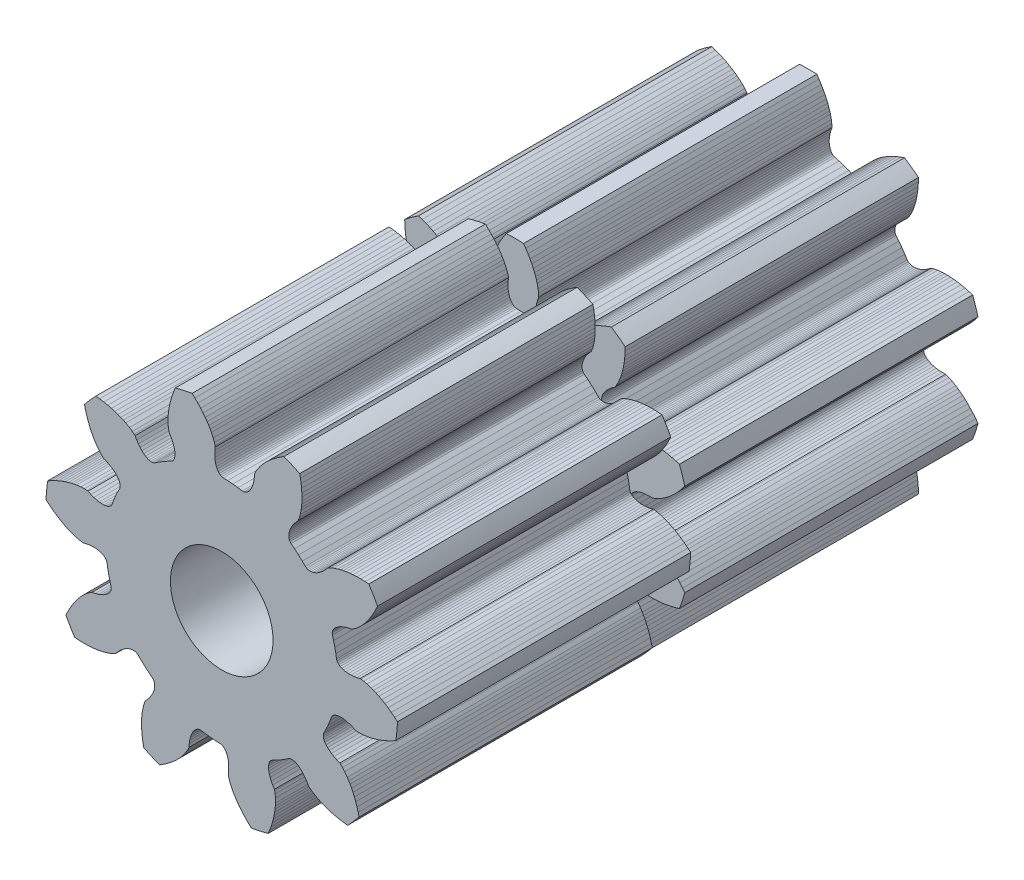
SolidWorks part; units mm, degrees
ref_plane "Front Plane" through (0, 0, 0) normal (0, 0, 1) x (1, 0, 0)
ref_plane "Top Plane" through (0, 0, 0) normal (0, 1, 0) x (1, 0, 0)
ref_plane "Right Plane" through (0, 0, 0) normal (1, 0, 0) x (0, 0, -1)
sketch "Sketch1" plane through (0, 0, 0) normal (0, 0, 1) x (1, 0, 0)
  line L0 (11.2428, -4.5485) -> (11.2517, -4.4039)
  line L1 (11.2517, -4.4039) -> (11.266, -4.2669)
  line L2 (11.266, -4.2669) -> (11.2847, -4.1393)
  line L3 (11.2847, -4.1393) -> (11.3071, -4.0209)
  line L4 (11.3071, -4.0209) -> (11.3325, -3.912)
  line L5 (11.3325, -3.912) -> (11.3608, -3.8103)
  line L6 (11.3608, -3.8103) -> (11.3897, -3.7211)
  line L7 (11.3897, -3.7211) -> (11.4208, -3.6371)
  line L8 (11.4208, -3.6371) -> (11.4807, -3.5016)
  line L9 (11.4807, -3.5016) -> (11.5377, -3.3971)
  line L10 (11.5377, -3.3971) -> (11.5845, -3.3262)
  line L11 (11.5845, -3.3262) -> (11.6076, -3.2964)
  line L12 (11.6076, -3.2964) -> (11.7007, -3.2317)
  line L13 (11.7007, -3.2317) -> (11.7827, -3.1653)
  line L14 (11.7827, -3.1653) -> (11.8533, -3.098)
  line L15 (11.8533, -3.098) -> (11.9128, -3.0308)
  line L16 (11.9128, -3.0308) -> (11.9612, -2.9643)
  line L17 (11.9612, -2.9643) -> (11.9989, -2.8995)
  line L18 (11.9989, -2.8995) -> (12.0259, -2.837)
  line L19 (12.0259, -2.837) -> (12.0426, -2.7776)
  line L20 (12.0426, -2.7776) -> (12.0493, -2.7222)
  line L21 (12.0493, -2.7222) -> (12.0463, -2.6714)
  line L22 (12.0463, -2.6714) -> (12.0342, -2.6259)
  line L23 (12.0342, -2.6259) -> (12.0067, -2.5776)
  line L24 (12.0067, -2.5776) -> (11.9109, -2.4617)
  line L25 (11.9109, -2.4617) -> (11.8044, -2.3217)
  line L26 (11.8044, -2.3217) -> (11.7041, -2.1772)
  line L27 (11.7041, -2.1772) -> (11.6236, -2.0503)
  line L28 (11.6236, -2.0503) -> (11.5861, -2.0092)
  line L29 (11.5861, -2.0092) -> (11.5466, -1.9836)
  line L30 (11.5466, -1.9836) -> (11.4992, -1.9651)
  line L31 (11.4992, -1.9651) -> (11.4444, -1.9543)
  line L32 (11.4444, -1.9543) -> (11.3828, -1.9518)
  line L33 (11.3828, -1.9518) -> (11.315, -1.9582)
  line L34 (11.315, -1.9582) -> (11.2417, -1.974)
  line L35 (11.2417, -1.974) -> (11.1635, -1.9995)
  line L36 (11.1635, -1.9995) -> (11.0812, -2.0353)
  line L37 (11.0812, -2.0353) -> (10.9954, -2.0817)
  line L38 (10.9954, -2.0817) -> (10.907, -2.1391)
  line L39 (10.907, -2.1391) -> (10.8166, -2.2077)
  line L40 (10.8166, -2.2077) -> (10.7811, -2.2204)
  line L41 (10.7811, -2.2204) -> (10.6992, -2.243)
  line L42 (10.6992, -2.243) -> (10.5823, -2.2649)
  line L43 (10.5823, -2.2649) -> (10.4348, -2.2801)
  line L44 (10.4348, -2.2801) -> (10.3453, -2.2837)
  line L45 (10.3453, -2.2837) -> (10.2516, -2.2836)
  line L46 (10.2516, -2.2836) -> (10.1461, -2.2791)
  line L47 (10.1461, -2.2791) -> (10.0348, -2.2696)
  line L48 (10.0348, -2.2696) -> (9.9151, -2.2543)
  line L49 (9.9151, -2.2543) -> (9.7881, -2.2327)
  line L50 (9.7881, -2.2327) -> (9.6533, -2.2039)
  line L51 (9.6533, -2.2039) -> (9.5131, -2.1677)
  line L52 (9.5131, -2.1677) -> (9.3912, -2.1311)
  line L53 (9.2098, -1.5726) -> (9.2868, -1.4714)
  line L54 (9.2868, -1.4714) -> (9.379, -1.3597)
  line L55 (9.379, -1.3597) -> (9.4711, -1.2572)
  line L56 (9.4711, -1.2572) -> (9.5612, -1.165)
  line L57 (9.5612, -1.165) -> (9.649, -1.0823)
  line L58 (9.649, -1.0823) -> (9.7335, -1.0092)
  line L59 (9.7335, -1.0092) -> (9.8162, -0.9435)
  line L60 (9.8162, -0.9435) -> (9.8919, -0.8883)
  line L61 (9.8919, -0.8883) -> (9.9665, -0.8387)
  line L62 (9.9665, -0.8387) -> (10.0947, -0.7642)
  line L63 (10.0947, -0.7642) -> (10.2021, -0.7133)
  line L64 (10.2021, -0.7133) -> (10.2817, -0.6834)
  line L65 (10.2817, -0.6834) -> (10.3179, -0.6728)
  line L66 (10.3179, -0.6728) -> (10.4313, -0.6752)
  line L67 (10.4313, -0.6752) -> (10.5366, -0.6696)
  line L68 (10.5366, -0.6696) -> (10.6333, -0.6568)
  line L69 (10.6333, -0.6568) -> (10.7209, -0.6373)
  line L70 (10.7209, -0.6373) -> (10.7992, -0.612)
  line L71 (10.7992, -0.612) -> (10.8678, -0.5817)
  line L72 (10.8678, -0.5817) -> (10.9263, -0.547)
  line L73 (10.9263, -0.547) -> (10.9747, -0.5088)
  line L74 (10.9747, -0.5088) -> (11.0127, -0.4679)
  line L75 (11.0127, -0.4679) -> (11.0402, -0.4251)
  line L76 (11.0402, -0.4251) -> (11.0571, -0.3811)
  line L77 (11.0571, -0.3811) -> (11.0633, -0.3259)
  line L78 (11.0633, -0.3259) -> (11.0539, -0.1759)
  line L79 (11.0539, -0.1759) -> (11.05, 0)
  line L80 (11.05, 0) -> (11.0539, 0.1759)
  line L81 (11.0539, 0.1759) -> (11.0633, 0.3259)
  line L82 (11.0633, 0.3259) -> (11.0571, 0.3812)
  line L83 (11.0571, 0.3812) -> (11.0402, 0.4251)
  line L84 (11.0402, 0.4251) -> (11.0127, 0.468)
  line L85 (11.0127, 0.468) -> (10.9747, 0.5089)
  line L86 (10.9747, 0.5089) -> (10.9263, 0.5471)
  line L87 (10.9263, 0.5471) -> (10.8678, 0.5817)
  line L88 (10.8678, 0.5817) -> (10.7992, 0.6121)
  line L89 (10.7992, 0.6121) -> (10.7209, 0.6374)
  line L90 (10.7209, 0.6374) -> (10.6333, 0.6568)
  line L91 (10.6333, 0.6568) -> (10.5366, 0.6697)
  line L92 (10.5366, 0.6697) -> (10.4313, 0.6753)
  line L93 (10.4313, 0.6753) -> (10.3179, 0.6729)
  line L94 (10.3179, 0.6729) -> (10.2817, 0.6834)
  line L95 (10.2817, 0.6834) -> (10.2021, 0.7133)
  line L96 (10.2021, 0.7133) -> (10.0947, 0.7643)
  line L97 (10.0947, 0.7643) -> (9.9665, 0.8387)
  line L98 (9.9665, 0.8387) -> (9.8919, 0.8884)
  line L99 (9.8919, 0.8884) -> (9.8162, 0.9436)
  line L100 (9.8162, 0.9436) -> (9.7335, 1.0093)
  line L101 (9.7335, 1.0093) -> (9.649, 1.0824)
  line L102 (9.649, 1.0824) -> (9.5612, 1.165)
  line L103 (9.5612, 1.165) -> (9.4711, 1.2572)
  line L104 (9.4711, 1.2572) -> (9.379, 1.3597)
  line L105 (9.379, 1.3597) -> (9.2868, 1.4714)
  line L106 (9.2868, 1.4714) -> (9.2098, 1.5727)
  line L107 (9.3912, 2.1311) -> (9.5131, 2.1677)
  line L108 (9.5131, 2.1677) -> (9.6533, 2.2039)
  line L109 (9.6533, 2.2039) -> (9.788, 2.2327)
  line L110 (9.788, 2.2327) -> (9.9151, 2.2544)
  line L111 (9.9151, 2.2544) -> (10.0347, 2.2696)
  line L112 (10.0347, 2.2696) -> (10.1461, 2.2791)
  line L113 (10.1461, 2.2791) -> (10.2516, 2.2836)
  line L114 (10.2516, 2.2836) -> (10.3453, 2.2837)
  line L115 (10.3453, 2.2837) -> (10.4348, 2.2801)
  line L116 (10.4348, 2.2801) -> (10.5823, 2.265)
  line L117 (10.5823, 2.265) -> (10.6992, 2.2431)
  line L118 (10.6992, 2.2431) -> (10.7811, 2.2205)
  line L119 (10.7811, 2.2205) -> (10.8166, 2.2078)
  line L120 (10.8166, 2.2078) -> (10.9069, 2.1391)
  line L121 (10.9069, 2.1391) -> (10.9954, 2.0818)
  line L122 (10.9954, 2.0818) -> (11.0812, 2.0353)
  line L123 (11.0812, 2.0353) -> (11.1635, 1.9995)
  line L124 (11.1635, 1.9995) -> (11.2417, 1.974)
  line L125 (11.2417, 1.974) -> (11.315, 1.9583)
  line L126 (11.315, 1.9583) -> (11.3828, 1.9519)
  line L127 (11.3828, 1.9519) -> (11.4444, 1.9543)
  line L128 (11.4444, 1.9543) -> (11.4991, 1.9651)
  line L129 (11.4991, 1.9651) -> (11.5465, 1.9836)
  line L130 (11.5465, 1.9836) -> (11.586, 2.0092)
  line L131 (11.586, 2.0092) -> (11.6235, 2.0503)
  line L132 (11.6235, 2.0503) -> (11.7041, 2.1772)
  line L133 (11.7041, 2.1772) -> (11.8043, 2.3218)
  line L134 (11.8043, 2.3218) -> (11.9109, 2.4618)
  line L135 (11.9109, 2.4618) -> (12.0067, 2.5776)
  line L136 (12.0067, 2.5776) -> (12.0341, 2.626)
  line L137 (12.0341, 2.626) -> (12.0463, 2.6715)
  line L138 (12.0463, 2.6715) -> (12.0492, 2.7223)
  line L139 (12.0492, 2.7223) -> (12.0426, 2.7777)
  line L140 (12.0426, 2.7777) -> (12.0259, 2.837)
  line L141 (12.0259, 2.837) -> (11.9988, 2.8995)
  line L142 (11.9988, 2.8995) -> (11.9612, 2.9643)
  line L143 (11.9612, 2.9643) -> (11.9128, 3.0308)
  line L144 (11.9128, 3.0308) -> (11.8533, 3.0981)
  line L145 (11.8533, 3.0981) -> (11.7826, 3.1653)
  line L146 (11.7826, 3.1653) -> (11.7007, 3.2317)
  line L147 (11.7007, 3.2317) -> (11.6075, 3.2964)
  line L148 (11.6075, 3.2964) -> (11.5845, 3.3262)
  line L149 (11.5845, 3.3262) -> (11.5377, 3.3972)
  line L150 (11.5377, 3.3972) -> (11.4807, 3.5016)
  line L151 (11.4807, 3.5016) -> (11.4208, 3.6372)
  line L152 (11.4208, 3.6372) -> (11.3896, 3.7212)
  line L153 (11.3896, 3.7212) -> (11.3608, 3.8103)
  line L154 (11.3608, 3.8103) -> (11.3325, 3.9121)
  line L155 (11.3325, 3.9121) -> (11.3071, 4.0209)
  line L156 (11.3071, 4.0209) -> (11.2846, 4.1394)
  line L157 (11.2846, 4.1394) -> (11.2659, 4.2669)
  line L158 (11.2659, 4.2669) -> (11.2517, 4.404)
  line L159 (11.2517, 4.404) -> (11.2428, 4.5485)
  line L160 (11.2428, 4.5485) -> (11.2399, 4.6757)
  line L161 (11.715, 5.0209) -> (11.8351, 4.9789)
  line L162 (11.8351, 4.9789) -> (11.9698, 4.9257)
  line L163 (11.9698, 4.9257) -> (12.0958, 4.8698)
  line L164 (12.0958, 4.8698) -> (12.2113, 4.8127)
  line L165 (12.2113, 4.8127) -> (12.3171, 4.7547)
  line L166 (12.3171, 4.7547) -> (12.4127, 4.6969)
  line L167 (12.4127, 4.6969) -> (12.5007, 4.6385)
  line L168 (12.5007, 4.6385) -> (12.5766, 4.5836)
  line L169 (12.5766, 4.5836) -> (12.6469, 4.528)
  line L170 (12.6469, 4.528) -> (12.7573, 4.4291)
  line L171 (12.7573, 4.4291) -> (12.839, 4.3427)
  line L172 (12.839, 4.3427) -> (12.892, 4.2762)
  line L173 (12.892, 4.2762) -> (12.9132, 4.2451)
  line L174 (12.9132, 4.2451) -> (12.946, 4.1364)
  line L175 (12.946, 4.1364) -> (12.9838, 4.038)
  line L176 (12.9838, 4.038) -> (13.0259, 3.9501)
  line L177 (13.0259, 3.9501) -> (13.0715, 3.8727)
  line L178 (13.0715, 3.8727) -> (13.1197, 3.8061)
  line L179 (13.1197, 3.8061) -> (13.1698, 3.7503)
  line L180 (13.1698, 3.7503) -> (13.2209, 3.7053)
  line L181 (13.2209, 3.7053) -> (13.2721, 3.671)
  line L182 (13.2721, 3.671) -> (13.3228, 3.6476)
  line L183 (13.3228, 3.6476) -> (13.372, 3.6347)
  line L184 (13.372, 3.6347) -> (13.419, 3.6322)
  line L185 (13.419, 3.6322) -> (13.4735, 3.6434)
  line L186 (13.4735, 3.6434) -> (13.6133, 3.6987)
  line L187 (13.6133, 3.6987) -> (13.7794, 3.7567)
  line L188 (13.7794, 3.7567) -> (13.9478, 3.8074)
  line L189 (13.9478, 3.8074) -> (14.0934, 3.8448)
  line L190 (14.0934, 3.8448) -> (14.1441, 3.8678)
  line L191 (14.1441, 3.8678) -> (14.1806, 3.8974)
  line L192 (14.1806, 3.8974) -> (14.2129, 3.9368)
  line L193 (14.2129, 3.9368) -> (14.2401, 3.9855)
  line L194 (14.2401, 3.9855) -> (14.2614, 4.0434)
  line L195 (14.2614, 4.0434) -> (14.2763, 4.1098)
  line L196 (14.2763, 4.1098) -> (14.284, 4.1844)
  line L197 (14.284, 4.1844) -> (14.2838, 4.2666)
  line L198 (14.2838, 4.2666) -> (14.2752, 4.356)
  line L199 (14.2752, 4.356) -> (14.2576, 4.4519)
  line L200 (14.2576, 4.4519) -> (14.2304, 4.5538)
  line L201 (14.2304, 4.5538) -> (14.193, 4.6609)
  line L202 (14.193, 4.6609) -> (14.1919, 4.6986)
  line L203 (14.1919, 4.6986) -> (14.1957, 4.7835)
  line L204 (14.1957, 4.7835) -> (14.211, 4.9014)
  line L205 (14.211, 4.9014) -> (14.2422, 5.0463)
  line L206 (14.2422, 5.0463) -> (14.2664, 5.1326)
  line L207 (14.2664, 5.1326) -> (14.2955, 5.2217)
  line L208 (14.2955, 5.2217) -> (14.3324, 5.3207)
  line L209 (14.3324, 5.3207) -> (14.3758, 5.4236)
  line L210 (14.3758, 5.4236) -> (14.4273, 5.5327)
  line L211 (14.4273, 5.5327) -> (14.4871, 5.6468)
  line L212 (14.4871, 5.6468) -> (14.5562, 5.7661)
  line L213 (14.5562, 5.7661) -> (14.6339, 5.8883)
  line L214 (14.6339, 5.8883) -> (14.7064, 5.9928)
  line L215 (15.2936, 5.9928) -> (15.3661, 5.8883)
  line L216 (15.3661, 5.8883) -> (15.4438, 5.7661)
  line L217 (15.4438, 5.7661) -> (15.5128, 5.6468)
  line L218 (15.5128, 5.6468) -> (15.5727, 5.5327)
  line L219 (15.5727, 5.5327) -> (15.6242, 5.4236)
  line L220 (15.6242, 5.4236) -> (15.6676, 5.3207)
  line L221 (15.6676, 5.3207) -> (15.7045, 5.2217)
  line L222 (15.7045, 5.2217) -> (15.7336, 5.1326)
  line L223 (15.7336, 5.1326) -> (15.7578, 5.0464)
  line L224 (15.7578, 5.0464) -> (15.7889, 4.9014)
  line L225 (15.7889, 4.9014) -> (15.8042, 4.7835)
  line L226 (15.8042, 4.7835) -> (15.8081, 4.6986)
  line L227 (15.8081, 4.6986) -> (15.8069, 4.6609)
  line L228 (15.8069, 4.6609) -> (15.7696, 4.5538)
  line L229 (15.7696, 4.5538) -> (15.7424, 4.4519)
  line L230 (15.7424, 4.4519) -> (15.7247, 4.356)
  line L231 (15.7247, 4.356) -> (15.7161, 4.2666)
  line L232 (15.7161, 4.2666) -> (15.716, 4.1844)
  line L233 (15.716, 4.1844) -> (15.7237, 4.1098)
  line L234 (15.7237, 4.1098) -> (15.7385, 4.0434)
  line L235 (15.7385, 4.0434) -> (15.7599, 3.9855)
  line L236 (15.7599, 3.9855) -> (15.7871, 3.9368)
  line L237 (15.7871, 3.9368) -> (15.8193, 3.8974)
  line L238 (15.8193, 3.8974) -> (15.8559, 3.8678)
  line L239 (15.8559, 3.8678) -> (15.9065, 3.8448)
  line L240 (15.9065, 3.8448) -> (16.0521, 3.8074)
  line L241 (16.0521, 3.8074) -> (16.2206, 3.7567)
  line L242 (16.2206, 3.7567) -> (16.3867, 3.6987)
  line L243 (16.3867, 3.6987) -> (16.5264, 3.6434)
  line L244 (16.5264, 3.6434) -> (16.5809, 3.6322)
  line L245 (16.5809, 3.6322) -> (16.6279, 3.6347)
  line L246 (16.6279, 3.6347) -> (16.6772, 3.6476)
  line L247 (16.6772, 3.6476) -> (16.7278, 3.6711)
  line L248 (16.7278, 3.6711) -> (16.7791, 3.7053)
  line L249 (16.7791, 3.7053) -> (16.8301, 3.7503)
  line L250 (16.8301, 3.7503) -> (16.8802, 3.8061)
  line L251 (16.8802, 3.8061) -> (16.9284, 3.8727)
  line L252 (16.9284, 3.8727) -> (16.974, 3.9501)
  line L253 (16.974, 3.9501) -> (17.0161, 4.038)
  line L254 (17.0161, 4.038) -> (17.054, 4.1365)
  line L255 (17.054, 4.1365) -> (17.0867, 4.2451)
  line L256 (17.0867, 4.2451) -> (17.108, 4.2762)
  line L257 (17.108, 4.2762) -> (17.161, 4.3427)
  line L258 (17.161, 4.3427) -> (17.2427, 4.4291)
  line L259 (17.2427, 4.4291) -> (17.3531, 4.528)
  line L260 (17.3531, 4.528) -> (17.4233, 4.5836)
  line L261 (17.4233, 4.5836) -> (17.4992, 4.6385)
  line L262 (17.4992, 4.6385) -> (17.5873, 4.6969)
  line L263 (17.5873, 4.6969) -> (17.6829, 4.7547)
  line L264 (17.6829, 4.7547) -> (17.7886, 4.8127)
  line L265 (17.7886, 4.8127) -> (17.9042, 4.8699)
  line L266 (17.9042, 4.8699) -> (18.0301, 4.9258)
  line L267 (18.0301, 4.9258) -> (18.1648, 4.9789)
  line L268 (18.1648, 4.9789) -> (18.2849, 5.0209)
  line L269 (18.76, 4.6758) -> (18.7572, 4.5486)
  line L270 (18.7572, 4.5486) -> (18.7483, 4.404)
  line L271 (18.7483, 4.404) -> (18.734, 4.2669)
  line L272 (18.734, 4.2669) -> (18.7153, 4.1394)
  line L273 (18.7153, 4.1394) -> (18.6928, 4.0209)
  line L274 (18.6928, 4.0209) -> (18.6675, 3.9121)
  line L275 (18.6675, 3.9121) -> (18.6392, 3.8103)
  line L276 (18.6392, 3.8103) -> (18.6103, 3.7212)
  line L277 (18.6103, 3.7212) -> (18.5792, 3.6372)
  line L278 (18.5792, 3.6372) -> (18.5192, 3.5016)
  line L279 (18.5192, 3.5016) -> (18.4623, 3.3972)
  line L280 (18.4623, 3.3972) -> (18.4155, 3.3263)
  line L281 (18.4155, 3.3263) -> (18.3924, 3.2965)
  line L282 (18.3924, 3.2965) -> (18.2992, 3.2317)
  line L283 (18.2992, 3.2317) -> (18.2173, 3.1653)
  line L284 (18.2173, 3.1653) -> (18.1467, 3.0981)
  line L285 (18.1467, 3.0981) -> (18.0872, 3.0308)
  line L286 (18.0872, 3.0308) -> (18.0387, 2.9644)
  line L287 (18.0387, 2.9644) -> (18.0011, 2.8995)
  line L288 (18.0011, 2.8995) -> (17.9741, 2.837)
  line L289 (17.9741, 2.837) -> (17.9574, 2.7777)
  line L290 (17.9574, 2.7777) -> (17.9507, 2.7223)
  line L291 (17.9507, 2.7223) -> (17.9537, 2.6715)
  line L292 (17.9537, 2.6715) -> (17.9658, 2.626)
  line L293 (17.9658, 2.626) -> (17.9933, 2.5777)
  line L294 (17.9933, 2.5777) -> (18.0891, 2.4618)
  line L295 (18.0891, 2.4618) -> (18.1956, 2.3218)
  line L296 (18.1956, 2.3218) -> (18.2959, 2.1772)
  line L297 (18.2959, 2.1772) -> (18.3764, 2.0503)
  line L298 (18.3764, 2.0503) -> (18.4139, 2.0093)
  line L299 (18.4139, 2.0093) -> (18.4534, 1.9836)
  line L300 (18.4534, 1.9836) -> (18.5008, 1.9651)
  line L301 (18.5008, 1.9651) -> (18.5556, 1.9544)
  line L302 (18.5556, 1.9544) -> (18.6172, 1.9519)
  line L303 (18.6172, 1.9519) -> (18.6849, 1.9583)
  line L304 (18.6849, 1.9583) -> (18.7583, 1.974)
  line L305 (18.7583, 1.974) -> (18.8364, 1.9996)
  line L306 (18.8364, 1.9996) -> (18.9188, 2.0354)
  line L307 (18.9188, 2.0354) -> (19.0046, 2.0818)
  line L308 (19.0046, 2.0818) -> (19.093, 2.1392)
  line L309 (19.093, 2.1392) -> (19.1834, 2.2078)
  line L310 (19.1834, 2.2078) -> (19.2188, 2.2205)
  line L311 (19.2188, 2.2205) -> (19.3008, 2.2431)
  line L312 (19.3008, 2.2431) -> (19.4177, 2.265)
  line L313 (19.4177, 2.265) -> (19.5651, 2.2801)
  line L314 (19.5651, 2.2801) -> (19.6547, 2.2838)
  line L315 (19.6547, 2.2838) -> (19.7484, 2.2837)
  line L316 (19.7484, 2.2837) -> (19.8539, 2.2791)
  line L317 (19.8539, 2.2791) -> (19.9652, 2.2696)
  line L318 (19.9652, 2.2696) -> (20.0848, 2.2544)
  line L319 (20.0848, 2.2544) -> (20.2119, 2.2328)
  line L320 (20.2119, 2.2328) -> (20.3467, 2.204)
  line L321 (20.3467, 2.204) -> (20.4869, 2.1678)
  line L322 (20.4869, 2.1678) -> (20.6088, 2.1312)
  line L323 (20.7902, 1.5727) -> (20.7132, 1.4714)
  line L324 (20.7132, 1.4714) -> (20.621, 1.3598)
  line L325 (20.621, 1.3598) -> (20.5289, 1.2572)
  line L326 (20.5289, 1.2572) -> (20.4388, 1.165)
  line L327 (20.4388, 1.165) -> (20.351, 1.0824)
  line L328 (20.351, 1.0824) -> (20.2665, 1.0093)
  line L329 (20.2665, 1.0093) -> (20.1838, 0.9436)
  line L330 (20.1838, 0.9436) -> (20.108, 0.8884)
  line L331 (20.108, 0.8884) -> (20.0335, 0.8388)
  line L332 (20.0335, 0.8388) -> (19.9053, 0.7643)
  line L333 (19.9053, 0.7643) -> (19.7979, 0.7133)
  line L334 (19.7979, 0.7133) -> (19.7183, 0.6834)
  line L335 (19.7183, 0.6834) -> (19.6821, 0.6729)
  line L336 (19.6821, 0.6729) -> (19.5687, 0.6753)
  line L337 (19.5687, 0.6753) -> (19.4634, 0.6697)
  line L338 (19.4634, 0.6697) -> (19.3667, 0.6568)
  line L339 (19.3667, 0.6568) -> (19.279, 0.6374)
  line L340 (19.279, 0.6374) -> (19.2008, 0.6121)
  line L341 (19.2008, 0.6121) -> (19.1322, 0.5818)
  line L342 (19.1322, 0.5818) -> (19.0736, 0.5471)
  line L343 (19.0736, 0.5471) -> (19.0253, 0.5089)
  line L344 (19.0253, 0.5089) -> (18.9873, 0.468)
  line L345 (18.9873, 0.468) -> (18.9598, 0.4252)
  line L346 (18.9598, 0.4252) -> (18.9429, 0.3812)
  line L347 (18.9429, 0.3812) -> (18.9367, 0.3259)
  line L348 (18.9367, 0.3259) -> (18.9461, 0.1759)
  line L349 (18.9461, 0.1759) -> (18.95, 0)
  line L350 (18.95, 0) -> (18.9461, -0.1758)
  line L351 (18.9461, -0.1758) -> (18.9367, -0.3259)
  line L352 (18.9367, -0.3259) -> (18.9429, -0.3811)
  line L353 (18.9429, -0.3811) -> (18.9598, -0.4251)
  line L354 (18.9598, -0.4251) -> (18.9873, -0.4679)
  line L355 (18.9873, -0.4679) -> (19.0253, -0.5088)
  line L356 (19.0253, -0.5088) -> (19.0736, -0.547)
  line L357 (19.0736, -0.547) -> (19.1322, -0.5817)
  line L358 (19.1322, -0.5817) -> (19.2008, -0.612)
  line L359 (19.2008, -0.612) -> (19.279, -0.6373)
  line L360 (19.279, -0.6373) -> (19.3667, -0.6567)
  line L361 (19.3667, -0.6567) -> (19.4634, -0.6696)
  line L362 (19.4634, -0.6696) -> (19.5687, -0.6752)
  line L363 (19.5687, -0.6752) -> (19.6821, -0.6728)
  line L364 (19.6821, -0.6728) -> (19.7183, -0.6834)
  line L365 (19.7183, -0.6834) -> (19.7979, -0.7132)
  line L366 (19.7979, -0.7132) -> (19.9053, -0.7642)
  line L367 (19.9053, -0.7642) -> (20.0335, -0.8387)
  line L368 (20.0335, -0.8387) -> (20.108, -0.8883)
  line L369 (20.108, -0.8883) -> (20.1838, -0.9435)
  line L370 (20.1838, -0.9435) -> (20.2665, -1.0092)
  line L371 (20.2665, -1.0092) -> (20.351, -1.0823)
  line L372 (20.351, -1.0823) -> (20.4388, -1.1649)
  line L373 (20.4388, -1.1649) -> (20.5289, -1.2571)
  line L374 (20.5289, -1.2571) -> (20.621, -1.3597)
  line L375 (20.621, -1.3597) -> (20.7132, -1.4714)
  line L376 (20.7132, -1.4714) -> (20.7902, -1.5726)
  line L377 (20.6088, -2.131) -> (20.4869, -2.1677)
  line L378 (20.4869, -2.1677) -> (20.3467, -2.2039)
  line L379 (20.3467, -2.2039) -> (20.2119, -2.2327)
  line L380 (20.2119, -2.2327) -> (20.0849, -2.2543)
  line L381 (20.0849, -2.2543) -> (19.9652, -2.2695)
  line L382 (19.9652, -2.2695) -> (19.8539, -2.279)
  line L383 (19.8539, -2.279) -> (19.7484, -2.2836)
  line L384 (19.7484, -2.2836) -> (19.6547, -2.2837)
  line L385 (19.6547, -2.2837) -> (19.5652, -2.28)
  line L386 (19.5652, -2.28) -> (19.4177, -2.2649)
  line L387 (19.4177, -2.2649) -> (19.3008, -2.243)
  line L388 (19.3008, -2.243) -> (19.2189, -2.2204)
  line L389 (19.2189, -2.2204) -> (19.1834, -2.2077)
  line L390 (19.1834, -2.2077) -> (19.093, -2.1391)
  line L391 (19.093, -2.1391) -> (19.0046, -2.0817)
  line L392 (19.0046, -2.0817) -> (18.9188, -2.0353)
  line L393 (18.9188, -2.0353) -> (18.8365, -1.9995)
  line L394 (18.8365, -1.9995) -> (18.7583, -1.9739)
  line L395 (18.7583, -1.9739) -> (18.685, -1.9582)
  line L396 (18.685, -1.9582) -> (18.6172, -1.9518)
  line L397 (18.6172, -1.9518) -> (18.5556, -1.9543)
  line L398 (18.5556, -1.9543) -> (18.5008, -1.965)
  line L399 (18.5008, -1.965) -> (18.4534, -1.9835)
  line L400 (18.4534, -1.9835) -> (18.4139, -2.0092)
  line L401 (18.4139, -2.0092) -> (18.3764, -2.0502)
  line L402 (18.3764, -2.0502) -> (18.2959, -2.1771)
  line L403 (18.2959, -2.1771) -> (18.1956, -2.3217)
  line L404 (18.1956, -2.3217) -> (18.0891, -2.4617)
  line L405 (18.0891, -2.4617) -> (17.9933, -2.5776)
  line L406 (17.9933, -2.5776) -> (17.9658, -2.6259)
  line L407 (17.9658, -2.6259) -> (17.9537, -2.6714)
  line L408 (17.9537, -2.6714) -> (17.9507, -2.7222)
  line L409 (17.9507, -2.7222) -> (17.9574, -2.7776)
  line L410 (17.9574, -2.7776) -> (17.9741, -2.8369)
  line L411 (17.9741, -2.8369) -> (18.0011, -2.8994)
  line L412 (18.0011, -2.8994) -> (18.0387, -2.9643)
  line L413 (18.0387, -2.9643) -> (18.0872, -3.0307)
  line L414 (18.0872, -3.0307) -> (18.1467, -3.098)
  line L415 (18.1467, -3.098) -> (18.2173, -3.1652)
  line L416 (18.2173, -3.1652) -> (18.2992, -3.2316)
  line L417 (18.2992, -3.2316) -> (18.3924, -3.2964)
  line L418 (18.3924, -3.2964) -> (18.4155, -3.3262)
  line L419 (18.4155, -3.3262) -> (18.4623, -3.3971)
  line L420 (18.4623, -3.3971) -> (18.5193, -3.5015)
  line L421 (18.5193, -3.5015) -> (18.5792, -3.6371)
  line L422 (18.5792, -3.6371) -> (18.6103, -3.7211)
  line L423 (18.6103, -3.7211) -> (18.6392, -3.8102)
  line L424 (18.6392, -3.8102) -> (18.6675, -3.912)
  line L425 (18.6675, -3.912) -> (18.6929, -4.0208)
  line L426 (18.6929, -4.0208) -> (18.7153, -4.1393)
  line L427 (18.7153, -4.1393) -> (18.734, -4.2668)
  line L428 (18.734, -4.2668) -> (18.7483, -4.4039)
  line L429 (18.7483, -4.4039) -> (18.7572, -4.5484)
  line L430 (18.7572, -4.5484) -> (18.76, -4.6757)
  line L431 (18.285, -5.0208) -> (18.1648, -4.9788)
  line L432 (18.1648, -4.9788) -> (18.0301, -4.9257)
  line L433 (18.0301, -4.9257) -> (17.9042, -4.8698)
  line L434 (17.9042, -4.8698) -> (17.7886, -4.8126)
  line L435 (17.7886, -4.8126) -> (17.6829, -4.7546)
  line L436 (17.6829, -4.7546) -> (17.5873, -4.6968)
  line L437 (17.5873, -4.6968) -> (17.4992, -4.6385)
  line L438 (17.4992, -4.6385) -> (17.4234, -4.5835)
  line L439 (17.4234, -4.5835) -> (17.3531, -4.5279)
  line L440 (17.3531, -4.5279) -> (17.2427, -4.429)
  line L441 (17.2427, -4.429) -> (17.161, -4.3426)
  line L442 (17.161, -4.3426) -> (17.108, -4.2761)
  line L443 (17.108, -4.2761) -> (17.0868, -4.245)
  line L444 (17.0868, -4.245) -> (17.054, -4.1364)
  line L445 (17.054, -4.1364) -> (17.0161, -4.038)
  line L446 (17.0161, -4.038) -> (16.974, -3.95)
  line L447 (16.974, -3.95) -> (16.9284, -3.8726)
  line L448 (16.9284, -3.8726) -> (16.8802, -3.806)
  line L449 (16.8802, -3.806) -> (16.8302, -3.7502)
  line L450 (16.8302, -3.7502) -> (16.7791, -3.7052)
  line L451 (16.7791, -3.7052) -> (16.7278, -3.671)
  line L452 (16.7278, -3.671) -> (16.6772, -3.6475)
  line L453 (16.6772, -3.6475) -> (16.6279, -3.6346)
  line L454 (16.6279, -3.6346) -> (16.5809, -3.6321)
  line L455 (16.5809, -3.6321) -> (16.5265, -3.6433)
  line L456 (16.5265, -3.6433) -> (16.3867, -3.6986)
  line L457 (16.3867, -3.6986) -> (16.2206, -3.7567)
  line L458 (16.2206, -3.7567) -> (16.0521, -3.8073)
  line L459 (16.0521, -3.8073) -> (15.9066, -3.8447)
  line L460 (15.9066, -3.8447) -> (15.8559, -3.8677)
  line L461 (15.8559, -3.8677) -> (15.8193, -3.8973)
  line L462 (15.8193, -3.8973) -> (15.7871, -3.9367)
  line L463 (15.7871, -3.9367) -> (15.7599, -3.9855)
  line L464 (15.7599, -3.9855) -> (15.7385, -4.0433)
  line L465 (15.7385, -4.0433) -> (15.7237, -4.1097)
  line L466 (15.7237, -4.1097) -> (15.716, -4.1843)
  line L467 (15.716, -4.1843) -> (15.7161, -4.2665)
  line L468 (15.7161, -4.2665) -> (15.7247, -4.3559)
  line L469 (15.7247, -4.3559) -> (15.7424, -4.4518)
  line L470 (15.7424, -4.4518) -> (15.7696, -4.5537)
  line L471 (15.7696, -4.5537) -> (15.8069, -4.6609)
  line L472 (15.8069, -4.6609) -> (15.8081, -4.6985)
  line L473 (15.8081, -4.6985) -> (15.8042, -4.7834)
  line L474 (15.8042, -4.7834) -> (15.789, -4.9014)
  line L475 (15.789, -4.9014) -> (15.7578, -5.0463)
  line L476 (15.7578, -5.0463) -> (15.7336, -5.1325)
  line L477 (15.7336, -5.1325) -> (15.7045, -5.2216)
  line L478 (15.7045, -5.2216) -> (15.6676, -5.3206)
  line L479 (15.6676, -5.3206) -> (15.6242, -5.4235)
  line L480 (15.6242, -5.4235) -> (15.5727, -5.5326)
  line L481 (15.5727, -5.5326) -> (15.5129, -5.6468)
  line L482 (15.5129, -5.6468) -> (15.4438, -5.766)
  line L483 (15.4438, -5.766) -> (15.3661, -5.8882)
  line L484 (15.3661, -5.8882) -> (15.2936, -5.9928)
  line L485 (14.7064, -5.9928) -> (14.6339, -5.8882)
  line L486 (14.6339, -5.8882) -> (14.5561, -5.766)
  line L487 (14.5561, -5.766) -> (14.4871, -5.6468)
  line L488 (14.4871, -5.6468) -> (14.4272, -5.5326)
  line L489 (14.4272, -5.5326) -> (14.3758, -5.4235)
  line L490 (14.3758, -5.4235) -> (14.3324, -5.3206)
  line L491 (14.3324, -5.3206) -> (14.2954, -5.2216)
  line L492 (14.2954, -5.2216) -> (14.2664, -5.1325)
  line L493 (14.2664, -5.1325) -> (14.2422, -5.0463)
  line L494 (14.2422, -5.0463) -> (14.211, -4.9014)
  line L495 (14.211, -4.9014) -> (14.1957, -4.7834)
  line L496 (14.1957, -4.7834) -> (14.1919, -4.6985)
  line L497 (14.1919, -4.6985) -> (14.193, -4.6608)
  line L498 (14.193, -4.6608) -> (14.2304, -4.5537)
  line L499 (14.2304, -4.5537) -> (14.2576, -4.4518)
  line L500 (14.2576, -4.4518) -> (14.2752, -4.3559)
  line L501 (14.2752, -4.3559) -> (14.2838, -4.2665)
  line L502 (14.2838, -4.2665) -> (14.284, -4.1843)
  line L503 (14.284, -4.1843) -> (14.2763, -4.1097)
  line L504 (14.2763, -4.1097) -> (14.2614, -4.0433)
  line L505 (14.2614, -4.0433) -> (14.24, -3.9855)
  line L506 (14.24, -3.9855) -> (14.2129, -3.9367)
  line L507 (14.2129, -3.9367) -> (14.1806, -3.8973)
  line L508 (14.1806, -3.8973) -> (14.144, -3.8677)
  line L509 (14.144, -3.8677) -> (14.0934, -3.8447)
  line L510 (14.0934, -3.8447) -> (13.9478, -3.8073)
  line L511 (13.9478, -3.8073) -> (13.7793, -3.7567)
  line L512 (13.7793, -3.7567) -> (13.6133, -3.6986)
  line L513 (13.6133, -3.6986) -> (13.4735, -3.6433)
  line L514 (13.4735, -3.6433) -> (13.419, -3.6321)
  line L515 (13.419, -3.6321) -> (13.372, -3.6346)
  line L516 (13.372, -3.6346) -> (13.3228, -3.6475)
  line L517 (13.3228, -3.6475) -> (13.2721, -3.671)
  line L518 (13.2721, -3.671) -> (13.2209, -3.7052)
  line L519 (13.2209, -3.7052) -> (13.1698, -3.7502)
  line L520 (13.1698, -3.7502) -> (13.1197, -3.806)
  line L521 (13.1197, -3.806) -> (13.0715, -3.8726)
  line L522 (13.0715, -3.8726) -> (13.0259, -3.95)
  line L523 (13.0259, -3.95) -> (12.9838, -4.038)
  line L524 (12.9838, -4.038) -> (12.946, -4.1364)
  line L525 (12.946, -4.1364) -> (12.9132, -4.245)
  line L526 (12.9132, -4.245) -> (12.892, -4.2761)
  line L527 (12.892, -4.2761) -> (12.839, -4.3426)
  line L528 (12.839, -4.3426) -> (12.7573, -4.429)
  line L529 (12.7573, -4.429) -> (12.6469, -4.5279)
  line L530 (12.6469, -4.5279) -> (12.5766, -4.5835)
  line L531 (12.5766, -4.5835) -> (12.5007, -4.6385)
  line L532 (12.5007, -4.6385) -> (12.4127, -4.6968)
  line L533 (12.4127, -4.6968) -> (12.317, -4.7546)
  line L534 (12.317, -4.7546) -> (12.2113, -4.8126)
  line L535 (12.2113, -4.8126) -> (12.0958, -4.8698)
  line L536 (12.0958, -4.8698) -> (11.9698, -4.9257)
  line L537 (11.9698, -4.9257) -> (11.8351, -4.9788)
  line L538 (11.8351, -4.9788) -> (11.715, -5.0208)
  line L539 (11.24, -4.6757) -> (11.2428, -4.5485)
  line L540 (11.2428, -4.5485) -> (11.2517, -4.4039)
  line L541 (11.2517, -4.4039) -> (11.266, -4.2669)
  line L542 (11.266, -4.2669) -> (11.2847, -4.1393)
  line L543 (11.2847, -4.1393) -> (11.3071, -4.0209)
  line L544 (11.3071, -4.0209) -> (11.3325, -3.912)
  line L545 (11.3325, -3.912) -> (11.3608, -3.8103)
  line L546 (11.3608, -3.8103) -> (11.3897, -3.7211)
  line L547 (11.3897, -3.7211) -> (11.4208, -3.6371)
  line L548 (11.4208, -3.6371) -> (11.4807, -3.5016)
  line L549 (11.4807, -3.5016) -> (11.5377, -3.3971)
  line L550 (11.5377, -3.3971) -> (11.5845, -3.3262)
  line L551 (11.5845, -3.3262) -> (11.6076, -3.2964)
  line L552 (11.6076, -3.2964) -> (11.7007, -3.2317)
  line L553 (11.7007, -3.2317) -> (11.7827, -3.1653)
  line L554 (11.7827, -3.1653) -> (11.8533, -3.098)
  line L555 (11.8533, -3.098) -> (11.9128, -3.0308)
  line L556 (11.9128, -3.0308) -> (11.9612, -2.9643)
  line L557 (11.9612, -2.9643) -> (11.9989, -2.8995)
  line L558 (11.9989, -2.8995) -> (12.0259, -2.837)
  line L559 (12.0259, -2.837) -> (12.0426, -2.7776)
  line L560 (12.0426, -2.7776) -> (12.0493, -2.7222)
  line L561 (12.0493, -2.7222) -> (12.0463, -2.6714)
  line L562 (12.0463, -2.6714) -> (12.0342, -2.6259)
  line L563 (12.0342, -2.6259) -> (12.0067, -2.5776)
  line L564 (12.0067, -2.5776) -> (11.9109, -2.4617)
  line L565 (11.9109, -2.4617) -> (11.8044, -2.3217)
  line L566 (11.8044, -2.3217) -> (11.7041, -2.1772)
  line L567 (11.7041, -2.1772) -> (11.6236, -2.0503)
  line L568 (11.6236, -2.0503) -> (11.5861, -2.0092)
  line L569 (11.5861, -2.0092) -> (11.5466, -1.9836)
  line L570 (11.5466, -1.9836) -> (11.4992, -1.9651)
  line L571 (11.4992, -1.9651) -> (11.4444, -1.9543)
  line L572 (11.4444, -1.9543) -> (11.3828, -1.9518)
  line L573 (11.3828, -1.9518) -> (11.315, -1.9582)
  line L574 (11.315, -1.9582) -> (11.2417, -1.974)
  line L575 (11.2417, -1.974) -> (11.1635, -1.9995)
  line L576 (11.1635, -1.9995) -> (11.0812, -2.0353)
  line L577 (11.0812, -2.0353) -> (10.9954, -2.0817)
  line L578 (10.9954, -2.0817) -> (10.907, -2.1391)
  line L579 (10.907, -2.1391) -> (10.8166, -2.2077)
  line L580 (10.8166, -2.2077) -> (10.7811, -2.2204)
  line L581 (10.7811, -2.2204) -> (10.6992, -2.243)
  line L582 (10.6992, -2.243) -> (10.5823, -2.2649)
  line L583 (10.5823, -2.2649) -> (10.4348, -2.2801)
  line L584 (10.4348, -2.2801) -> (10.3453, -2.2837)
  line L585 (10.3453, -2.2837) -> (10.2516, -2.2836)
  line L586 (10.2516, -2.2836) -> (10.1461, -2.2791)
  line L587 (10.1461, -2.2791) -> (10.0348, -2.2696)
  line L588 (10.0348, -2.2696) -> (9.9151, -2.2543)
  line L589 (9.9151, -2.2543) -> (9.7881, -2.2327)
  line L590 (9.7881, -2.2327) -> (9.6533, -2.2039)
  line L591 (9.6533, -2.2039) -> (9.5131, -2.1677)
  line L592 (9.5131, -2.1677) -> (9.3912, -2.1311)
  line L593 (9.2098, -1.5726) -> (9.2868, -1.4714)
  line L594 (9.2868, -1.4714) -> (9.379, -1.3597)
  line L595 (9.379, -1.3597) -> (9.4711, -1.2572)
  line L596 (9.4711, -1.2572) -> (9.5612, -1.165)
  line L597 (9.5612, -1.165) -> (9.649, -1.0823)
  line L598 (9.649, -1.0823) -> (9.7335, -1.0092)
  line L599 (9.7335, -1.0092) -> (9.8162, -0.9435)
  line L600 (9.8162, -0.9435) -> (9.8919, -0.8883)
  line L601 (9.8919, -0.8883) -> (9.9665, -0.8387)
  line L602 (9.9665, -0.8387) -> (10.0947, -0.7642)
  line L603 (10.0947, -0.7642) -> (10.2021, -0.7133)
  line L604 (10.2021, -0.7133) -> (10.2817, -0.6834)
  line L605 (10.2817, -0.6834) -> (10.3179, -0.6728)
  line L606 (10.3179, -0.6728) -> (10.4313, -0.6752)
  line L607 (10.4313, -0.6752) -> (10.5366, -0.6696)
  line L608 (10.5366, -0.6696) -> (10.6333, -0.6568)
  line L609 (10.6333, -0.6568) -> (10.7209, -0.6373)
  line L610 (10.7209, -0.6373) -> (10.7992, -0.612)
  line L611 (10.7992, -0.612) -> (10.8678, -0.5817)
  line L612 (10.8678, -0.5817) -> (10.9263, -0.547)
  line L613 (10.9263, -0.547) -> (10.9747, -0.5088)
  line L614 (10.9747, -0.5088) -> (11.0127, -0.4679)
  line L615 (11.0127, -0.4679) -> (11.0402, -0.4251)
  line L616 (11.0402, -0.4251) -> (11.0571, -0.3811)
  line L617 (11.0571, -0.3811) -> (11.0633, -0.3259)
  line L618 (11.0633, -0.3259) -> (11.0539, -0.1759)
  line L619 (11.0539, -0.1759) -> (11.05, 0)
  line L620 (11.05, 0) -> (11.0539, 0.1759)
  line L621 (11.0539, 0.1759) -> (11.0633, 0.3259)
  line L622 (11.0633, 0.3259) -> (11.0571, 0.3812)
  line L623 (11.0571, 0.3812) -> (11.0402, 0.4251)
  line L624 (11.0402, 0.4251) -> (11.0127, 0.468)
  line L625 (11.0127, 0.468) -> (10.9747, 0.5089)
  line L626 (10.9747, 0.5089) -> (10.9263, 0.5471)
  line L627 (10.9263, 0.5471) -> (10.8678, 0.5817)
  line L628 (10.8678, 0.5817) -> (10.7992, 0.6121)
  line L629 (10.7992, 0.6121) -> (10.7209, 0.6374)
  line L630 (10.7209, 0.6374) -> (10.6333, 0.6568)
  line L631 (10.6333, 0.6568) -> (10.5366, 0.6697)
  line L632 (10.5366, 0.6697) -> (10.4313, 0.6753)
  line L633 (10.4313, 0.6753) -> (10.3179, 0.6729)
  line L634 (10.3179, 0.6729) -> (10.2817, 0.6834)
  line L635 (10.2817, 0.6834) -> (10.2021, 0.7133)
  line L636 (10.2021, 0.7133) -> (10.0947, 0.7643)
  line L637 (10.0947, 0.7643) -> (9.9665, 0.8387)
  line L638 (9.9665, 0.8387) -> (9.8919, 0.8884)
  line L639 (9.8919, 0.8884) -> (9.8162, 0.9436)
  line L640 (9.8162, 0.9436) -> (9.7335, 1.0093)
  line L641 (9.7335, 1.0093) -> (9.649, 1.0824)
  line L642 (9.649, 1.0824) -> (9.5612, 1.165)
  line L643 (9.5612, 1.165) -> (9.4711, 1.2572)
  line L644 (9.4711, 1.2572) -> (9.379, 1.3597)
  line L645 (9.379, 1.3597) -> (9.2868, 1.4714)
  line L646 (9.2868, 1.4714) -> (9.2098, 1.5727)
  line L647 (9.3912, 2.1311) -> (9.5131, 2.1677)
  line L648 (9.5131, 2.1677) -> (9.6533, 2.2039)
  line L649 (9.6533, 2.2039) -> (9.788, 2.2327)
  line L650 (9.788, 2.2327) -> (9.9151, 2.2544)
  line L651 (9.9151, 2.2544) -> (10.0347, 2.2696)
  line L652 (10.0347, 2.2696) -> (10.1461, 2.2791)
  line L653 (10.1461, 2.2791) -> (10.2516, 2.2836)
  line L654 (10.2516, 2.2836) -> (10.3453, 2.2837)
  line L655 (10.3453, 2.2837) -> (10.4348, 2.2801)
  line L656 (10.4348, 2.2801) -> (10.5823, 2.265)
  line L657 (10.5823, 2.265) -> (10.6992, 2.2431)
  line L658 (10.6992, 2.2431) -> (10.7811, 2.2205)
  line L659 (10.7811, 2.2205) -> (10.8166, 2.2078)
  line L660 (10.8166, 2.2078) -> (10.9069, 2.1391)
  line L661 (10.9069, 2.1391) -> (10.9954, 2.0818)
  line L662 (10.9954, 2.0818) -> (11.0812, 2.0353)
  line L663 (11.0812, 2.0353) -> (11.1635, 1.9995)
  line L664 (11.1635, 1.9995) -> (11.2417, 1.974)
  line L665 (11.2417, 1.974) -> (11.315, 1.9583)
  line L666 (11.315, 1.9583) -> (11.3828, 1.9519)
  line L667 (11.3828, 1.9519) -> (11.4444, 1.9543)
  line L668 (11.4444, 1.9543) -> (11.4991, 1.9651)
  line L669 (11.4991, 1.9651) -> (11.5465, 1.9836)
  line L670 (11.5465, 1.9836) -> (11.586, 2.0092)
  line L671 (11.586, 2.0092) -> (11.6235, 2.0503)
  line L672 (11.6235, 2.0503) -> (11.7041, 2.1772)
  line L673 (11.7041, 2.1772) -> (11.8043, 2.3218)
  line L674 (11.8043, 2.3218) -> (11.9109, 2.4618)
  line L675 (11.9109, 2.4618) -> (12.0067, 2.5776)
  line L676 (12.0067, 2.5776) -> (12.0341, 2.626)
  line L677 (12.0341, 2.626) -> (12.0463, 2.6715)
  line L678 (12.0463, 2.6715) -> (12.0492, 2.7223)
  line L679 (12.0492, 2.7223) -> (12.0426, 2.7777)
  line L680 (12.0426, 2.7777) -> (12.0259, 2.837)
  line L681 (12.0259, 2.837) -> (11.9988, 2.8995)
  line L682 (11.9988, 2.8995) -> (11.9612, 2.9643)
  line L683 (11.9612, 2.9643) -> (11.9128, 3.0308)
  line L684 (11.9128, 3.0308) -> (11.8533, 3.0981)
  line L685 (11.8533, 3.0981) -> (11.7826, 3.1653)
  line L686 (11.7826, 3.1653) -> (11.7007, 3.2317)
  line L687 (11.7007, 3.2317) -> (11.6075, 3.2964)
  line L688 (11.6075, 3.2964) -> (11.5845, 3.3262)
  line L689 (11.5845, 3.3262) -> (11.5377, 3.3972)
  line L690 (11.5377, 3.3972) -> (11.4807, 3.5016)
  line L691 (11.4807, 3.5016) -> (11.4208, 3.6372)
  line L692 (11.4208, 3.6372) -> (11.3896, 3.7212)
  line L693 (11.3896, 3.7212) -> (11.3608, 3.8103)
  line L694 (11.3608, 3.8103) -> (11.3325, 3.9121)
  line L695 (11.3325, 3.9121) -> (11.3071, 4.0209)
  line L696 (11.3071, 4.0209) -> (11.2846, 4.1394)
  line L697 (11.2846, 4.1394) -> (11.2659, 4.2669)
  line L698 (11.2659, 4.2669) -> (11.2517, 4.404)
  line L699 (11.2517, 4.404) -> (11.2428, 4.5485)
  line L700 (11.2428, 4.5485) -> (11.2399, 4.6757)
  line L701 (11.715, 5.0209) -> (11.8351, 4.9789)
  line L702 (11.8351, 4.9789) -> (11.9698, 4.9257)
  line L703 (11.9698, 4.9257) -> (12.0958, 4.8698)
  line L704 (12.0958, 4.8698) -> (12.2113, 4.8127)
  line L705 (12.2113, 4.8127) -> (12.3171, 4.7547)
  line L706 (12.3171, 4.7547) -> (12.4127, 4.6969)
  line L707 (12.4127, 4.6969) -> (12.5007, 4.6385)
  line L708 (12.5007, 4.6385) -> (12.5766, 4.5836)
  line L709 (12.5766, 4.5836) -> (12.6469, 4.528)
  line L710 (12.6469, 4.528) -> (12.7573, 4.4291)
  line L711 (12.7573, 4.4291) -> (12.839, 4.3427)
  line L712 (12.839, 4.3427) -> (12.892, 4.2762)
  line L713 (12.892, 4.2762) -> (12.9132, 4.2451)
  line L714 (12.9132, 4.2451) -> (12.946, 4.1364)
  line L715 (12.946, 4.1364) -> (12.9838, 4.038)
  line L716 (12.9838, 4.038) -> (13.0259, 3.9501)
  line L717 (13.0259, 3.9501) -> (13.0715, 3.8727)
  line L718 (13.0715, 3.8727) -> (13.1197, 3.8061)
  line L719 (13.1197, 3.8061) -> (13.1698, 3.7503)
  line L720 (13.1698, 3.7503) -> (13.2209, 3.7053)
  line L721 (13.2209, 3.7053) -> (13.2721, 3.671)
  line L722 (13.2721, 3.671) -> (13.3228, 3.6476)
  line L723 (13.3228, 3.6476) -> (13.372, 3.6347)
  line L724 (13.372, 3.6347) -> (13.419, 3.6322)
  line L725 (13.419, 3.6322) -> (13.4735, 3.6434)
  line L726 (13.4735, 3.6434) -> (13.6133, 3.6987)
  line L727 (13.6133, 3.6987) -> (13.7794, 3.7567)
  line L728 (13.7794, 3.7567) -> (13.9478, 3.8074)
  line L729 (13.9478, 3.8074) -> (14.0934, 3.8448)
  line L730 (14.0934, 3.8448) -> (14.1441, 3.8678)
  line L731 (14.1441, 3.8678) -> (14.1806, 3.8974)
  line L732 (14.1806, 3.8974) -> (14.2129, 3.9368)
  line L733 (14.2129, 3.9368) -> (14.2401, 3.9855)
  line L734 (14.2401, 3.9855) -> (14.2614, 4.0434)
  line L735 (14.2614, 4.0434) -> (14.2763, 4.1098)
  line L736 (14.2763, 4.1098) -> (14.284, 4.1844)
  line L737 (14.284, 4.1844) -> (14.2838, 4.2666)
  line L738 (14.2838, 4.2666) -> (14.2752, 4.356)
  line L739 (14.2752, 4.356) -> (14.2576, 4.4519)
  line L740 (14.2576, 4.4519) -> (14.2304, 4.5538)
  line L741 (14.2304, 4.5538) -> (14.193, 4.6609)
  line L742 (14.193, 4.6609) -> (14.1919, 4.6986)
  line L743 (14.1919, 4.6986) -> (14.1957, 4.7835)
  line L744 (14.1957, 4.7835) -> (14.211, 4.9014)
  line L745 (14.211, 4.9014) -> (14.2422, 5.0463)
  line L746 (14.2422, 5.0463) -> (14.2664, 5.1326)
  line L747 (14.2664, 5.1326) -> (14.2955, 5.2217)
  line L748 (14.2955, 5.2217) -> (14.3324, 5.3207)
  line L749 (14.3324, 5.3207) -> (14.3758, 5.4236)
  line L750 (14.3758, 5.4236) -> (14.4273, 5.5327)
  line L751 (14.4273, 5.5327) -> (14.4871, 5.6468)
  line L752 (14.4871, 5.6468) -> (14.5562, 5.7661)
  line L753 (14.5562, 5.7661) -> (14.6339, 5.8883)
  line L754 (14.6339, 5.8883) -> (14.7064, 5.9928)
  line L755 (15.2936, 5.9928) -> (15.3661, 5.8883)
  line L756 (15.3661, 5.8883) -> (15.4438, 5.7661)
  line L757 (15.4438, 5.7661) -> (15.5128, 5.6468)
  line L758 (15.5128, 5.6468) -> (15.5727, 5.5327)
  line L759 (15.5727, 5.5327) -> (15.6242, 5.4236)
  line L760 (15.6242, 5.4236) -> (15.6676, 5.3207)
  line L761 (15.6676, 5.3207) -> (15.7045, 5.2217)
  line L762 (15.7045, 5.2217) -> (15.7336, 5.1326)
  line L763 (15.7336, 5.1326) -> (15.7578, 5.0464)
  line L764 (15.7578, 5.0464) -> (15.7889, 4.9014)
  line L765 (15.7889, 4.9014) -> (15.8042, 4.7835)
  line L766 (15.8042, 4.7835) -> (15.8081, 4.6986)
  line L767 (15.8081, 4.6986) -> (15.8069, 4.6609)
  line L768 (15.8069, 4.6609) -> (15.7696, 4.5538)
  line L769 (15.7696, 4.5538) -> (15.7424, 4.4519)
  line L770 (15.7424, 4.4519) -> (15.7247, 4.356)
  line L771 (15.7247, 4.356) -> (15.7161, 4.2666)
  line L772 (15.7161, 4.2666) -> (15.716, 4.1844)
  line L773 (15.716, 4.1844) -> (15.7237, 4.1098)
  line L774 (15.7237, 4.1098) -> (15.7385, 4.0434)
  line L775 (15.7385, 4.0434) -> (15.7599, 3.9855)
  line L776 (15.7599, 3.9855) -> (15.7871, 3.9368)
  line L777 (15.7871, 3.9368) -> (15.8193, 3.8974)
  line L778 (15.8193, 3.8974) -> (15.8559, 3.8678)
  line L779 (15.8559, 3.8678) -> (15.9065, 3.8448)
  line L780 (15.9065, 3.8448) -> (16.0521, 3.8074)
  line L781 (16.0521, 3.8074) -> (16.2206, 3.7567)
  line L782 (16.2206, 3.7567) -> (16.3867, 3.6987)
  line L783 (16.3867, 3.6987) -> (16.5264, 3.6434)
  line L784 (16.5264, 3.6434) -> (16.5809, 3.6322)
  line L785 (16.5809, 3.6322) -> (16.6279, 3.6347)
  line L786 (16.6279, 3.6347) -> (16.6772, 3.6476)
  line L787 (16.6772, 3.6476) -> (16.7278, 3.6711)
  line L788 (16.7278, 3.6711) -> (16.7791, 3.7053)
  line L789 (16.7791, 3.7053) -> (16.8301, 3.7503)
  line L790 (16.8301, 3.7503) -> (16.8802, 3.8061)
  line L791 (16.8802, 3.8061) -> (16.9284, 3.8727)
  line L792 (16.9284, 3.8727) -> (16.974, 3.9501)
  line L793 (16.974, 3.9501) -> (17.0161, 4.038)
  line L794 (17.0161, 4.038) -> (17.054, 4.1365)
  line L795 (17.054, 4.1365) -> (17.0867, 4.2451)
  line L796 (17.0867, 4.2451) -> (17.108, 4.2762)
  line L797 (17.108, 4.2762) -> (17.161, 4.3427)
  line L798 (17.161, 4.3427) -> (17.2427, 4.4291)
  line L799 (17.2427, 4.4291) -> (17.3531, 4.528)
  line L800 (17.3531, 4.528) -> (17.4233, 4.5836)
  line L801 (17.4233, 4.5836) -> (17.4992, 4.6385)
  line L802 (17.4992, 4.6385) -> (17.5873, 4.6969)
  line L803 (17.5873, 4.6969) -> (17.6829, 4.7547)
  line L804 (17.6829, 4.7547) -> (17.7886, 4.8127)
  line L805 (17.7886, 4.8127) -> (17.9042, 4.8699)
  line L806 (17.9042, 4.8699) -> (18.0301, 4.9258)
  line L807 (18.0301, 4.9258) -> (18.1648, 4.9789)
  line L808 (18.1648, 4.9789) -> (18.2849, 5.0209)
  line L809 (18.76, 4.6758) -> (18.7572, 4.5486)
  line L810 (18.7572, 4.5486) -> (18.7483, 4.404)
  line L811 (18.7483, 4.404) -> (18.734, 4.2669)
  line L812 (18.734, 4.2669) -> (18.7153, 4.1394)
  line L813 (18.7153, 4.1394) -> (18.6928, 4.0209)
  line L814 (18.6928, 4.0209) -> (18.6675, 3.9121)
  line L815 (18.6675, 3.9121) -> (18.6392, 3.8103)
  line L816 (18.6392, 3.8103) -> (18.6103, 3.7212)
  line L817 (18.6103, 3.7212) -> (18.5792, 3.6372)
  line L818 (18.5792, 3.6372) -> (18.5192, 3.5016)
  line L819 (18.5192, 3.5016) -> (18.4623, 3.3972)
  line L820 (18.4623, 3.3972) -> (18.4155, 3.3263)
  line L821 (18.4155, 3.3263) -> (18.3924, 3.2965)
  line L822 (18.3924, 3.2965) -> (18.2992, 3.2317)
  line L823 (18.2992, 3.2317) -> (18.2173, 3.1653)
  line L824 (18.2173, 3.1653) -> (18.1467, 3.0981)
  line L825 (18.1467, 3.0981) -> (18.0872, 3.0308)
  line L826 (18.0872, 3.0308) -> (18.0387, 2.9644)
  line L827 (18.0387, 2.9644) -> (18.0011, 2.8995)
  line L828 (18.0011, 2.8995) -> (17.9741, 2.837)
  line L829 (17.9741, 2.837) -> (17.9574, 2.7777)
  line L830 (17.9574, 2.7777) -> (17.9507, 2.7223)
  line L831 (17.9507, 2.7223) -> (17.9537, 2.6715)
  line L832 (17.9537, 2.6715) -> (17.9658, 2.626)
  line L833 (17.9658, 2.626) -> (17.9933, 2.5777)
  line L834 (17.9933, 2.5777) -> (18.0891, 2.4618)
  line L835 (18.0891, 2.4618) -> (18.1956, 2.3218)
  line L836 (18.1956, 2.3218) -> (18.2959, 2.1772)
  line L837 (18.2959, 2.1772) -> (18.3764, 2.0503)
  line L838 (18.3764, 2.0503) -> (18.4139, 2.0093)
  line L839 (18.4139, 2.0093) -> (18.4534, 1.9836)
  line L840 (18.4534, 1.9836) -> (18.5008, 1.9651)
  line L841 (18.5008, 1.9651) -> (18.5556, 1.9544)
  line L842 (18.5556, 1.9544) -> (18.6172, 1.9519)
  line L843 (18.6172, 1.9519) -> (18.6849, 1.9583)
  line L844 (18.6849, 1.9583) -> (18.7583, 1.974)
  line L845 (18.7583, 1.974) -> (18.8364, 1.9996)
  line L846 (18.8364, 1.9996) -> (18.9188, 2.0354)
  line L847 (18.9188, 2.0354) -> (19.0046, 2.0818)
  line L848 (19.0046, 2.0818) -> (19.093, 2.1392)
  line L849 (19.093, 2.1392) -> (19.1834, 2.2078)
  line L850 (19.1834, 2.2078) -> (19.2188, 2.2205)
  line L851 (19.2188, 2.2205) -> (19.3008, 2.2431)
  line L852 (19.3008, 2.2431) -> (19.4177, 2.265)
  line L853 (19.4177, 2.265) -> (19.5651, 2.2801)
  line L854 (19.5651, 2.2801) -> (19.6547, 2.2838)
  line L855 (19.6547, 2.2838) -> (19.7484, 2.2837)
  line L856 (19.7484, 2.2837) -> (19.8539, 2.2791)
  line L857 (19.8539, 2.2791) -> (19.9652, 2.2696)
  line L858 (19.9652, 2.2696) -> (20.0848, 2.2544)
  line L859 (20.0848, 2.2544) -> (20.2119, 2.2328)
  line L860 (20.2119, 2.2328) -> (20.3467, 2.204)
  line L861 (20.3467, 2.204) -> (20.4869, 2.1678)
  line L862 (20.4869, 2.1678) -> (20.6088, 2.1312)
  line L863 (20.7902, 1.5727) -> (20.7132, 1.4714)
  line L864 (20.7132, 1.4714) -> (20.621, 1.3598)
  line L865 (20.621, 1.3598) -> (20.5289, 1.2572)
  line L866 (20.5289, 1.2572) -> (20.4388, 1.165)
  line L867 (20.4388, 1.165) -> (20.351, 1.0824)
  line L868 (20.351, 1.0824) -> (20.2665, 1.0093)
  line L869 (20.2665, 1.0093) -> (20.1838, 0.9436)
  line L870 (20.1838, 0.9436) -> (20.108, 0.8884)
  line L871 (20.108, 0.8884) -> (20.0335, 0.8388)
  line L872 (20.0335, 0.8388) -> (19.9053, 0.7643)
  line L873 (19.9053, 0.7643) -> (19.7979, 0.7133)
  line L874 (19.7979, 0.7133) -> (19.7183, 0.6834)
  line L875 (19.7183, 0.6834) -> (19.6821, 0.6729)
  line L876 (19.6821, 0.6729) -> (19.5687, 0.6753)
  line L877 (19.5687, 0.6753) -> (19.4634, 0.6697)
  line L878 (19.4634, 0.6697) -> (19.3667, 0.6568)
  line L879 (19.3667, 0.6568) -> (19.279, 0.6374)
  line L880 (19.279, 0.6374) -> (19.2008, 0.6121)
  line L881 (19.2008, 0.6121) -> (19.1322, 0.5818)
  line L882 (19.1322, 0.5818) -> (19.0736, 0.5471)
  line L883 (19.0736, 0.5471) -> (19.0253, 0.5089)
  line L884 (19.0253, 0.5089) -> (18.9873, 0.468)
  line L885 (18.9873, 0.468) -> (18.9598, 0.4252)
  line L886 (18.9598, 0.4252) -> (18.9429, 0.3812)
  line L887 (18.9429, 0.3812) -> (18.9367, 0.3259)
  line L888 (18.9367, 0.3259) -> (18.9461, 0.1759)
  line L889 (18.9461, 0.1759) -> (18.95, 0)
  line L890 (18.95, 0) -> (18.9461, -0.1758)
  line L891 (18.9461, -0.1758) -> (18.9367, -0.3259)
  line L892 (18.9367, -0.3259) -> (18.9429, -0.3811)
  line L893 (18.9429, -0.3811) -> (18.9598, -0.4251)
  line L894 (18.9598, -0.4251) -> (18.9873, -0.4679)
  line L895 (18.9873, -0.4679) -> (19.0253, -0.5088)
  line L896 (19.0253, -0.5088) -> (19.0736, -0.547)
  line L897 (19.0736, -0.547) -> (19.1322, -0.5817)
  line L898 (19.1322, -0.5817) -> (19.2008, -0.612)
  line L899 (19.2008, -0.612) -> (19.279, -0.6373)
  line L900 (19.279, -0.6373) -> (19.3667, -0.6567)
  line L901 (19.3667, -0.6567) -> (19.4634, -0.6696)
  line L902 (19.4634, -0.6696) -> (19.5687, -0.6752)
  line L903 (19.5687, -0.6752) -> (19.6821, -0.6728)
  line L904 (19.6821, -0.6728) -> (19.7183, -0.6834)
  line L905 (19.7183, -0.6834) -> (19.7979, -0.7132)
  line L906 (19.7979, -0.7132) -> (19.9053, -0.7642)
  line L907 (19.9053, -0.7642) -> (20.0335, -0.8387)
  line L908 (20.0335, -0.8387) -> (20.108, -0.8883)
  line L909 (20.108, -0.8883) -> (20.1838, -0.9435)
  line L910 (20.1838, -0.9435) -> (20.2665, -1.0092)
  line L911 (20.2665, -1.0092) -> (20.351, -1.0823)
  line L912 (20.351, -1.0823) -> (20.4388, -1.1649)
  line L913 (20.4388, -1.1649) -> (20.5289, -1.2571)
  line L914 (20.5289, -1.2571) -> (20.621, -1.3597)
  line L915 (20.621, -1.3597) -> (20.7132, -1.4714)
  line L916 (20.7132, -1.4714) -> (20.7902, -1.5726)
  line L917 (20.6088, -2.131) -> (20.4869, -2.1677)
  line L918 (20.4869, -2.1677) -> (20.3467, -2.2039)
  line L919 (20.3467, -2.2039) -> (20.2119, -2.2327)
  line L920 (20.2119, -2.2327) -> (20.0849, -2.2543)
  line L921 (20.0849, -2.2543) -> (19.9652, -2.2695)
  line L922 (19.9652, -2.2695) -> (19.8539, -2.279)
  line L923 (19.8539, -2.279) -> (19.7484, -2.2836)
  line L924 (19.7484, -2.2836) -> (19.6547, -2.2837)
  line L925 (19.6547, -2.2837) -> (19.5652, -2.28)
  line L926 (19.5652, -2.28) -> (19.4177, -2.2649)
  line L927 (19.4177, -2.2649) -> (19.3008, -2.243)
  line L928 (19.3008, -2.243) -> (19.2189, -2.2204)
  line L929 (19.2189, -2.2204) -> (19.1834, -2.2077)
  line L930 (19.1834, -2.2077) -> (19.093, -2.1391)
  line L931 (19.093, -2.1391) -> (19.0046, -2.0817)
  line L932 (19.0046, -2.0817) -> (18.9188, -2.0353)
  line L933 (18.9188, -2.0353) -> (18.8365, -1.9995)
  line L934 (18.8365, -1.9995) -> (18.7583, -1.9739)
  line L935 (18.7583, -1.9739) -> (18.685, -1.9582)
  line L936 (18.685, -1.9582) -> (18.6172, -1.9518)
  line L937 (18.6172, -1.9518) -> (18.5556, -1.9543)
  line L938 (18.5556, -1.9543) -> (18.5008, -1.965)
  line L939 (18.5008, -1.965) -> (18.4534, -1.9835)
  line L940 (18.4534, -1.9835) -> (18.4139, -2.0092)
  line L941 (18.4139, -2.0092) -> (18.3764, -2.0502)
  line L942 (18.3764, -2.0502) -> (18.2959, -2.1771)
  line L943 (18.2959, -2.1771) -> (18.1956, -2.3217)
  line L944 (18.1956, -2.3217) -> (18.0891, -2.4617)
  line L945 (18.0891, -2.4617) -> (17.9933, -2.5776)
  line L946 (17.9933, -2.5776) -> (17.9658, -2.6259)
  line L947 (17.9658, -2.6259) -> (17.9537, -2.6714)
  line L948 (17.9537, -2.6714) -> (17.9507, -2.7222)
  line L949 (17.9507, -2.7222) -> (17.9574, -2.7776)
  line L950 (17.9574, -2.7776) -> (17.9741, -2.8369)
  line L951 (17.9741, -2.8369) -> (18.0011, -2.8994)
  line L952 (18.0011, -2.8994) -> (18.0387, -2.9643)
  line L953 (18.0387, -2.9643) -> (18.0872, -3.0307)
  line L954 (18.0872, -3.0307) -> (18.1467, -3.098)
  line L955 (18.1467, -3.098) -> (18.2173, -3.1652)
  line L956 (18.2173, -3.1652) -> (18.2992, -3.2316)
  line L957 (18.2992, -3.2316) -> (18.3924, -3.2964)
  line L958 (18.3924, -3.2964) -> (18.4155, -3.3262)
  line L959 (18.4155, -3.3262) -> (18.4623, -3.3971)
  line L960 (18.4623, -3.3971) -> (18.5193, -3.5015)
  line L961 (18.5193, -3.5015) -> (18.5792, -3.6371)
  line L962 (18.5792, -3.6371) -> (18.6103, -3.7211)
  line L963 (18.6103, -3.7211) -> (18.6392, -3.8102)
  line L964 (18.6392, -3.8102) -> (18.6675, -3.912)
  line L965 (18.6675, -3.912) -> (18.6929, -4.0208)
  line L966 (18.6929, -4.0208) -> (18.7153, -4.1393)
  line L967 (18.7153, -4.1393) -> (18.734, -4.2668)
  line L968 (18.734, -4.2668) -> (18.7483, -4.4039)
  line L969 (18.7483, -4.4039) -> (18.7572, -4.5484)
  line L970 (18.7572, -4.5484) -> (18.76, -4.6757)
  line L971 (18.285, -5.0208) -> (18.1648, -4.9788)
  line L972 (18.1648, -4.9788) -> (18.0301, -4.9257)
  line L973 (18.0301, -4.9257) -> (17.9042, -4.8698)
  line L974 (17.9042, -4.8698) -> (17.7886, -4.8126)
  line L975 (17.7886, -4.8126) -> (17.6829, -4.7546)
  line L976 (17.6829, -4.7546) -> (17.5873, -4.6968)
  line L977 (17.5873, -4.6968) -> (17.4992, -4.6385)
  line L978 (17.4992, -4.6385) -> (17.4234, -4.5835)
  line L979 (17.4234, -4.5835) -> (17.3531, -4.5279)
  line L980 (17.3531, -4.5279) -> (17.2427, -4.429)
  line L981 (17.2427, -4.429) -> (17.161, -4.3426)
  line L982 (17.161, -4.3426) -> (17.108, -4.2761)
  line L983 (17.108, -4.2761) -> (17.0868, -4.245)
  line L984 (17.0868, -4.245) -> (17.054, -4.1364)
  line L985 (17.054, -4.1364) -> (17.0161, -4.038)
  line L986 (17.0161, -4.038) -> (16.974, -3.95)
  line L987 (16.974, -3.95) -> (16.9284, -3.8726)
  line L988 (16.9284, -3.8726) -> (16.8802, -3.806)
  line L989 (16.8802, -3.806) -> (16.8302, -3.7502)
  line L990 (16.8302, -3.7502) -> (16.7791, -3.7052)
  line L991 (16.7791, -3.7052) -> (16.7278, -3.671)
  line L992 (16.7278, -3.671) -> (16.6772, -3.6475)
  line L993 (16.6772, -3.6475) -> (16.6279, -3.6346)
  line L994 (16.6279, -3.6346) -> (16.5809, -3.6321)
  line L995 (16.5809, -3.6321) -> (16.5265, -3.6433)
  line L996 (16.5265, -3.6433) -> (16.3867, -3.6986)
  line L997 (16.3867, -3.6986) -> (16.2206, -3.7567)
  line L998 (16.2206, -3.7567) -> (16.0521, -3.8073)
  line L999 (16.0521, -3.8073) -> (15.9066, -3.8447)
  line L1000 (15.9066, -3.8447) -> (15.8559, -3.8677)
  line L1001 (15.8559, -3.8677) -> (15.8193, -3.8973)
  line L1002 (15.8193, -3.8973) -> (15.7871, -3.9367)
  line L1003 (15.7871, -3.9367) -> (15.7599, -3.9855)
  line L1004 (15.7599, -3.9855) -> (15.7385, -4.0433)
  line L1005 (15.7385, -4.0433) -> (15.7237, -4.1097)
  line L1006 (15.7237, -4.1097) -> (15.716, -4.1843)
  line L1007 (15.716, -4.1843) -> (15.7161, -4.2665)
  line L1008 (15.7161, -4.2665) -> (15.7247, -4.3559)
  line L1009 (15.7247, -4.3559) -> (15.7424, -4.4518)
  line L1010 (15.7424, -4.4518) -> (15.7696, -4.5537)
  line L1011 (15.7696, -4.5537) -> (15.8069, -4.6609)
  line L1012 (15.8069, -4.6609) -> (15.8081, -4.6985)
  line L1013 (15.8081, -4.6985) -> (15.8042, -4.7834)
  line L1014 (15.8042, -4.7834) -> (15.789, -4.9014)
  line L1015 (15.789, -4.9014) -> (15.7578, -5.0463)
  line L1016 (15.7578, -5.0463) -> (15.7336, -5.1325)
  line L1017 (15.7336, -5.1325) -> (15.7045, -5.2216)
  line L1018 (15.7045, -5.2216) -> (15.6676, -5.3206)
  line L1019 (15.6676, -5.3206) -> (15.6242, -5.4235)
  line L1020 (15.6242, -5.4235) -> (15.5727, -5.5326)
  line L1021 (15.5727, -5.5326) -> (15.5129, -5.6468)
  line L1022 (15.5129, -5.6468) -> (15.4438, -5.766)
  line L1023 (15.4438, -5.766) -> (15.3661, -5.8882)
  line L1024 (15.3661, -5.8882) -> (15.2936, -5.9928)
  line L1025 (14.7064, -5.9928) -> (14.6339, -5.8882)
  line L1026 (14.6339, -5.8882) -> (14.5561, -5.766)
  line L1027 (14.5561, -5.766) -> (14.4871, -5.6468)
  line L1028 (14.4871, -5.6468) -> (14.4272, -5.5326)
  line L1029 (14.4272, -5.5326) -> (14.3758, -5.4235)
  line L1030 (14.3758, -5.4235) -> (14.3324, -5.3206)
  line L1031 (14.3324, -5.3206) -> (14.2954, -5.2216)
  line L1032 (14.2954, -5.2216) -> (14.2664, -5.1325)
  line L1033 (14.2664, -5.1325) -> (14.2422, -5.0463)
  line L1034 (14.2422, -5.0463) -> (14.211, -4.9014)
  line L1035 (14.211, -4.9014) -> (14.1957, -4.7834)
  line L1036 (14.1957, -4.7834) -> (14.1919, -4.6985)
  line L1037 (14.1919, -4.6985) -> (14.193, -4.6608)
  line L1038 (14.193, -4.6608) -> (14.2304, -4.5537)
  line L1039 (14.2304, -4.5537) -> (14.2576, -4.4518)
  line L1040 (14.2576, -4.4518) -> (14.2752, -4.3559)
  line L1041 (14.2752, -4.3559) -> (14.2838, -4.2665)
  line L1042 (14.2838, -4.2665) -> (14.284, -4.1843)
  line L1043 (14.284, -4.1843) -> (14.2763, -4.1097)
  line L1044 (14.2763, -4.1097) -> (14.2614, -4.0433)
  line L1045 (14.2614, -4.0433) -> (14.24, -3.9855)
  line L1046 (14.24, -3.9855) -> (14.2129, -3.9367)
  line L1047 (14.2129, -3.9367) -> (14.1806, -3.8973)
  line L1048 (14.1806, -3.8973) -> (14.144, -3.8677)
  line L1049 (14.144, -3.8677) -> (14.0934, -3.8447)
  line L1050 (14.0934, -3.8447) -> (13.9478, -3.8073)
  line L1051 (13.9478, -3.8073) -> (13.7793, -3.7567)
  line L1052 (13.7793, -3.7567) -> (13.6133, -3.6986)
  line L1053 (13.6133, -3.6986) -> (13.4735, -3.6433)
  line L1054 (13.4735, -3.6433) -> (13.419, -3.6321)
  line L1055 (13.419, -3.6321) -> (13.372, -3.6346)
  line L1056 (13.372, -3.6346) -> (13.3228, -3.6475)
  line L1057 (13.3228, -3.6475) -> (13.2721, -3.671)
  line L1058 (13.2721, -3.671) -> (13.2209, -3.7052)
  line L1059 (13.2209, -3.7052) -> (13.1698, -3.7502)
  line L1060 (13.1698, -3.7502) -> (13.1197, -3.806)
  line L1061 (13.1197, -3.806) -> (13.0715, -3.8726)
  line L1062 (13.0715, -3.8726) -> (13.0259, -3.95)
  line L1063 (13.0259, -3.95) -> (12.9838, -4.038)
  line L1064 (12.9838, -4.038) -> (12.946, -4.1364)
  line L1065 (12.946, -4.1364) -> (12.9132, -4.245)
  line L1066 (12.9132, -4.245) -> (12.892, -4.2761)
  line L1067 (12.892, -4.2761) -> (12.839, -4.3426)
  line L1068 (12.839, -4.3426) -> (12.7573, -4.429)
  line L1069 (12.7573, -4.429) -> (12.6469, -4.5279)
  line L1070 (12.6469, -4.5279) -> (12.5766, -4.5835)
  line L1071 (12.5766, -4.5835) -> (12.5007, -4.6385)
  line L1072 (12.5007, -4.6385) -> (12.4127, -4.6968)
  line L1073 (12.4127, -4.6968) -> (12.317, -4.7546)
  line L1074 (12.317, -4.7546) -> (12.2113, -4.8126)
  line L1075 (12.2113, -4.8126) -> (12.0958, -4.8698)
  line L1076 (12.0958, -4.8698) -> (11.9698, -4.9257)
  line L1077 (11.9698, -4.9257) -> (11.8351, -4.9788)
  line L1078 (11.8351, -4.9788) -> (11.715, -5.0208)
  line L1079 (11.24, -4.6757) -> (11.2428, -4.5485)
  arc A0 (9.2098, -1.5726) -> (9.3912, -2.1311) centre (15, 0) ccw
  arc A1 (9.3912, 2.1311) -> (9.2098, 1.5727) centre (15, 0) ccw
  arc A2 (11.715, 5.0209) -> (11.2399, 4.6757) centre (15, 0) ccw
  arc A3 (15.2936, 5.9928) -> (14.7064, 5.9928) centre (15, 0) ccw
  arc A4 (18.76, 4.6758) -> (18.2849, 5.0209) centre (15, 0) ccw
  arc A5 (20.7902, 1.5727) -> (20.6088, 2.1312) centre (15, 0) ccw
  arc A6 (20.6088, -2.131) -> (20.7902, -1.5726) centre (15, 0) ccw
  arc A7 (18.285, -5.0208) -> (18.76, -4.6757) centre (15, 0) ccw
  arc A8 (14.7064, -5.9928) -> (15.2936, -5.9928) centre (15, 0) ccw
  arc A9 (11.24, -4.6757) -> (11.715, -5.0208) centre (15, 0) ccw
  arc A10 (9.2098, -1.5726) -> (9.3912, -2.1311) centre (15, 0) ccw
  arc A11 (9.3912, 2.1311) -> (9.2098, 1.5727) centre (15, 0) ccw
  arc A12 (11.715, 5.0209) -> (11.2399, 4.6757) centre (15, 0) ccw
  arc A13 (15.2936, 5.9928) -> (14.7064, 5.9928) centre (15, 0) ccw
  arc A14 (18.76, 4.6758) -> (18.2849, 5.0209) centre (15, 0) ccw
  arc A15 (20.7902, 1.5727) -> (20.6088, 2.1312) centre (15, 0) ccw
  arc A16 (20.6088, -2.131) -> (20.7902, -1.5726) centre (15, 0) ccw
  arc A17 (18.285, -5.0208) -> (18.76, -4.6757) centre (15, 0) ccw
  arc A18 (14.7064, -5.9928) -> (15.2936, -5.9928) centre (15, 0) ccw
  arc A19 (11.24, -4.6757) -> (11.715, -5.0208) centre (15, 0) ccw
extrude "Boss-Extrude1" add sketch "Sketch1" along normal blind 10 contours L539 A9 L538 L537 L536 L535 L534 L533 L532 L531 L530 L529 L528 L527 L526 L525 L524 L523 L522 L521 L520 L519 L518 L517 L516 L515 L514 L513 L512 L511 L510 L509 L508 L507 L506 L505 L504 L503 L502 L501 L500 L499 L498 L497 L496 L495 L494 L493 L492 L491 L490 region at (15, 0, 0)
sketch "Sketch2" plane through (0, 0, 10) normal (0, 0, 1) x (1, 0, 0)
  circle A0 centre (15, 0) radius 3.95 construction
  point P6 (15, 0)
sketch "Sketch3" plane through (0, 0, 10) normal (0, 0, 1) x (1, 0, 0)
  circle A0 centre (15, 0) radius 1.65
  dimension "D1" = 3.3
extrude "Cut-Extrude1" cut sketch "Sketch3" against normal up to surface (10 mm away) up to face at (15, 0, 0)
sketch "Sketch4" plane through (0, 0, 10) normal (0, 0, 1) x (1, 0, 0)
  line L1080 (12.3163, -5.2539) -> (12.3411, -5.3787)
  line L1081 (12.8796, -5.6128) -> (12.9877, -5.5458)
  line L1082 (12.9877, -5.5458) -> (13.1078, -5.4648)
  line L1083 (13.1078, -5.4648) -> (13.2186, -5.3829)
  line L1084 (13.2186, -5.3829) -> (13.319, -5.3021)
  line L1085 (13.319, -5.3021) -> (13.4097, -5.2226)
  line L1086 (13.4097, -5.2226) -> (13.4906, -5.1455)
  line L1087 (13.4906, -5.1455) -> (13.5639, -5.0695)
  line L1088 (13.5639, -5.0695) -> (13.6261, -4.9993)
  line L1089 (13.6261, -4.9993) -> (13.6827, -4.9299)
  line L1090 (13.6827, -4.9299) -> (13.7691, -4.8094)
  line L1091 (13.7691, -4.8094) -> (13.8301, -4.7074)
  line L1092 (13.8301, -4.7074) -> (13.8675, -4.631)
  line L1093 (13.8675, -4.631) -> (13.8815, -4.596)
  line L1094 (13.8815, -4.596) -> (13.8899, -4.4829)
  line L1095 (13.8899, -4.4829) -> (13.9056, -4.3786)
  line L1096 (13.9056, -4.3786) -> (13.9277, -4.2836)
  line L1097 (13.9277, -4.2836) -> (13.9554, -4.1982)
  line L1098 (13.9554, -4.1982) -> (13.9881, -4.1227)
  line L1099 (13.9881, -4.1227) -> (14.0249, -4.0574)
  line L1100 (14.0249, -4.0574) -> (14.065, -4.0024)
  line L1101 (14.065, -4.0024) -> (14.1076, -3.9579)
  line L1102 (14.1076, -3.9579) -> (14.152, -3.924)
  line L1103 (14.152, -3.924) -> (14.1973, -3.9008)
  line L1104 (14.1973, -3.9008) -> (14.2426, -3.8882)
  line L1105 (14.2426, -3.8882) -> (14.2982, -3.8873)
  line L1106 (14.2982, -3.8873) -> (14.4467, -3.9111)
  line L1107 (14.4467, -3.9111) -> (14.6214, -3.9318)
  line L1108 (14.6214, -3.9318) -> (14.7968, -3.9448)
  line L1109 (14.7968, -3.9448) -> (14.947, -3.9498)
  line L1110 (14.947, -3.9498) -> (15.0015, -3.9613)
  line L1111 (15.0015, -3.9613) -> (15.0436, -3.9823)
  line L1112 (15.0436, -3.9823) -> (15.0836, -4.0137)
  line L1113 (15.0836, -4.0137) -> (15.1207, -4.0555)
  line L1114 (15.1207, -4.0555) -> (15.154, -4.1073)
  line L1115 (15.154, -4.1073) -> (15.1829, -4.1689)
  line L1116 (15.1829, -4.1689) -> (15.2066, -4.2401)
  line L1117 (15.2066, -4.2401) -> (15.2242, -4.3204)
  line L1118 (15.2242, -4.3204) -> (15.2352, -4.4095)
  line L1119 (15.2352, -4.4095) -> (15.2387, -4.507)
  line L1120 (15.2387, -4.507) -> (15.2342, -4.6123)
  line L1121 (15.2342, -4.6123) -> (15.2209, -4.725)
  line L1122 (15.2209, -4.725) -> (15.228, -4.762)
  line L1123 (15.228, -4.762) -> (15.2501, -4.8441)
  line L1124 (15.2501, -4.8441) -> (15.2906, -4.9559)
  line L1125 (15.2906, -4.9559) -> (15.3524, -5.0907)
  line L1126 (15.3524, -5.0907) -> (15.3947, -5.1696)
  line L1127 (15.3947, -5.1696) -> (15.4423, -5.2503)
  line L1128 (15.4423, -5.2503) -> (15.4998, -5.339)
  line L1129 (15.4998, -5.339) -> (15.5645, -5.4301)
  line L1130 (15.5645, -5.4301) -> (15.6383, -5.5254)
  line L1131 (15.6383, -5.5254) -> (15.7214, -5.6239)
  line L1132 (15.7214, -5.6239) -> (15.8147, -5.7254)
  line L1133 (15.8147, -5.7254) -> (15.917, -5.8279)
  line L1134 (15.917, -5.8279) -> (16.0104, -5.9143)
  line L1135 (16.5837, -5.7872) -> (16.6318, -5.6694)
  line L1136 (16.6318, -5.6694) -> (16.6813, -5.5333)
  line L1137 (16.6813, -5.5333) -> (16.7229, -5.4019)
  line L1138 (16.7229, -5.4019) -> (16.7566, -5.2775)
  line L1139 (16.7566, -5.2775) -> (16.7832, -5.1599)
  line L1140 (16.7832, -5.1599) -> (16.8034, -5.05)
  line L1141 (16.8034, -5.05) -> (16.818, -4.9454)
  line L1142 (16.818, -4.9454) -> (16.8271, -4.8521)
  line L1143 (16.8271, -4.8521) -> (16.832, -4.7627)
  line L1144 (16.832, -4.7627) -> (16.8311, -4.6144)
  line L1145 (16.8311, -4.6144) -> (16.8205, -4.496)
  line L1146 (16.8205, -4.496) -> (16.8059, -4.4122)
  line L1147 (16.8059, -4.4122) -> (16.7966, -4.3757)
  line L1148 (16.7966, -4.3757) -> (16.737, -4.2792)
  line L1149 (16.737, -4.2792) -> (16.6883, -4.1856)
  line L1150 (16.6883, -4.1856) -> (16.6504, -4.0958)
  line L1151 (16.6504, -4.0958) -> (16.6226, -4.0104)
  line L1152 (16.6226, -4.0104) -> (16.6047, -3.9301)
  line L1153 (16.6047, -3.9301) -> (16.596, -3.8557)
  line L1154 (16.596, -3.8557) -> (16.5962, -3.7876)
  line L1155 (16.5962, -3.7876) -> (16.6045, -3.7265)
  line L1156 (16.6045, -3.7265) -> (16.6205, -3.673)
  line L1157 (16.6205, -3.673) -> (16.6434, -3.6276)
  line L1158 (16.6434, -3.6276) -> (16.6727, -3.5908)
  line L1159 (16.6727, -3.5908) -> (16.7172, -3.5574)
  line L1160 (16.7172, -3.5574) -> (16.8513, -3.4893)
  line L1161 (16.8513, -3.4893) -> (17.0048, -3.4034)
  line L1162 (17.0048, -3.4034) -> (17.1543, -3.3108)
  line L1163 (17.1543, -3.3108) -> (17.2788, -3.2266)
  line L1164 (17.2788, -3.2266) -> (17.3296, -3.2038)
  line L1165 (17.3296, -3.2038) -> (17.376, -3.1961)
  line L1166 (17.376, -3.1961) -> (17.4269, -3.198)
  line L1167 (17.4269, -3.198) -> (17.4814, -3.21)
  line L1168 (17.4814, -3.21) -> (17.5389, -3.2323)
  line L1169 (17.5389, -3.2323) -> (17.5985, -3.2652)
  line L1170 (17.5985, -3.2652) -> (17.6594, -3.3088)
  line L1171 (17.6594, -3.3088) -> (17.7209, -3.3634)
  line L1172 (17.7209, -3.3634) -> (17.7822, -3.4291)
  line L1173 (17.7822, -3.4291) -> (17.8423, -3.5059)
  line L1174 (17.8423, -3.5059) -> (17.9006, -3.5938)
  line L1175 (17.9006, -3.5938) -> (17.9561, -3.6927)
  line L1176 (17.9561, -3.6927) -> (17.9835, -3.7185)
  line L1177 (17.9835, -3.7185) -> (18.0497, -3.7719)
  line L1178 (18.0497, -3.7719) -> (18.1481, -3.8386)
  line L1179 (18.1481, -3.8386) -> (18.2773, -3.9113)
  line L1180 (18.2773, -3.9113) -> (18.358, -3.9503)
  line L1181 (18.358, -3.9503) -> (18.4439, -3.9876)
  line L1182 (18.4439, -3.9876) -> (18.5425, -4.0255)
  line L1183 (18.5425, -4.0255) -> (18.6484, -4.0612)
  line L1184 (18.6484, -4.0612) -> (18.7642, -4.0949)
  line L1185 (18.7642, -4.0949) -> (18.8894, -4.1258)
  line L1186 (18.8894, -4.1258) -> (19.0244, -4.1531)
  line L1187 (19.0244, -4.1531) -> (19.1674, -4.1758)
  line L1188 (19.1674, -4.1758) -> (19.2938, -4.1908)
  line L1189 (19.6829, -3.751) -> (19.6526, -3.6274)
  line L1190 (19.6526, -3.6274) -> (19.6126, -3.4882)
  line L1191 (19.6126, -3.4882) -> (19.569, -3.3575)
  line L1192 (19.569, -3.3575) -> (19.5232, -3.237)
  line L1193 (19.5232, -3.237) -> (19.4756, -3.1262)
  line L1194 (19.4756, -3.1262) -> (19.4273, -3.0255)
  line L1195 (19.4273, -3.0255) -> (19.3776, -2.9323)
  line L1196 (19.3776, -2.9323) -> (19.3302, -2.8515)
  line L1197 (19.3302, -2.8515) -> (19.2816, -2.7762)
  line L1198 (19.2816, -2.7762) -> (19.1937, -2.6568)
  line L1199 (19.1937, -2.6568) -> (19.1155, -2.5672)
  line L1200 (19.1155, -2.5672) -> (19.0544, -2.5081)
  line L1201 (19.0544, -2.5081) -> (19.0255, -2.484)
  line L1202 (19.0255, -2.484) -> (18.9205, -2.4409)
  line L1203 (18.9205, -2.4409) -> (18.8262, -2.3938)
  line L1204 (18.8262, -2.3938) -> (18.7426, -2.3435)
  line L1205 (18.7426, -2.3435) -> (18.67, -2.2907)
  line L1206 (18.67, -2.2907) -> (18.6083, -2.2363)
  line L1207 (18.6083, -2.2363) -> (18.5575, -2.1811)
  line L1208 (18.5575, -2.1811) -> (18.5176, -2.126)
  line L1209 (18.5176, -2.126) -> (18.4885, -2.0717)
  line L1210 (18.4885, -2.0717) -> (18.47, -2.019)
  line L1211 (18.47, -2.019) -> (18.4619, -1.9688)
  line L1212 (18.4619, -1.9688) -> (18.4639, -1.9217)
  line L1213 (18.4639, -1.9217) -> (18.4803, -1.8686)
  line L1214 (18.4803, -1.8686) -> (18.5487, -1.7347)
  line L1215 (18.5487, -1.7347) -> (18.6224, -1.575)
  line L1216 (18.6224, -1.575) -> (18.689, -1.4122)
  line L1217 (18.689, -1.4122) -> (18.7402, -1.2708)
  line L1218 (18.7402, -1.2708) -> (18.7679, -1.2226)
  line L1219 (18.7679, -1.2226) -> (18.8009, -1.189)
  line L1220 (18.8009, -1.189) -> (18.8432, -1.1607)
  line L1221 (18.8432, -1.1607) -> (18.8943, -1.1384)
  line L1222 (18.8943, -1.1384) -> (18.9539, -1.1226)
  line L1223 (18.9539, -1.1226) -> (19.0215, -1.1142)
  line L1224 (19.0215, -1.1142) -> (19.0964, -1.1137)
  line L1225 (19.0964, -1.1137) -> (19.1783, -1.1217)
  line L1226 (19.1783, -1.1217) -> (19.2664, -1.1388)
  line L1227 (19.2664, -1.1388) -> (19.3602, -1.1656)
  line L1228 (19.3602, -1.1656) -> (19.459, -1.2025)
  line L1229 (19.459, -1.2025) -> (19.5621, -1.2499)
  line L1230 (19.5621, -1.2499) -> (19.5994, -1.2546)
  line L1231 (19.5994, -1.2546) -> (19.6843, -1.259)
  line L1232 (19.6843, -1.259) -> (19.8032, -1.255)
  line L1233 (19.8032, -1.255) -> (19.9504, -1.2379)
  line L1234 (19.9504, -1.2379) -> (20.0386, -1.2221)
  line L1235 (20.0386, -1.2221) -> (20.1301, -1.2017)
  line L1236 (20.1301, -1.2017) -> (20.2321, -1.1744)
  line L1237 (20.2321, -1.1744) -> (20.3388, -1.1411)
  line L1238 (20.3388, -1.1411) -> (20.4523, -1.1003)
  line L1239 (20.4523, -1.1003) -> (20.5716, -1.0517)
  line L1240 (20.5716, -1.0517) -> (20.697, -0.9944)
  line L1241 (20.697, -0.9944) -> (20.826, -0.9287)
  line L1242 (20.826, -0.9287) -> (20.9371, -0.8666)
  line L1243 (20.9934, -0.2821) -> (20.8962, -0.1999)
  line L1244 (20.8962, -0.1999) -> (20.782, -0.1108)
  line L1245 (20.782, -0.1108) -> (20.6699, -0.0307)
  line L1246 (20.6699, -0.0307) -> (20.562, 0.0398)
  line L1247 (20.562, 0.0398) -> (20.4584, 0.1015)
  line L1248 (20.4584, 0.1015) -> (20.3601, 0.1546)
  line L1249 (20.3601, 0.1546) -> (20.2651, 0.2008)
  line L1250 (20.2651, 0.2008) -> (20.1792, 0.2383)
  line L1251 (20.1792, 0.2383) -> (20.0957, 0.2707)
  line L1252 (20.0957, 0.2707) -> (19.9544, 0.3156)
  line L1253 (19.9544, 0.3156) -> (19.8385, 0.3421)
  line L1254 (19.8385, 0.3421) -> (19.7543, 0.3541)
  line L1255 (19.7543, 0.3541) -> (19.7168, 0.3566)
  line L1256 (19.7168, 0.3566) -> (19.6065, 0.3297)
  line L1257 (19.6065, 0.3297) -> (19.5025, 0.3123)
  line L1258 (19.5025, 0.3123) -> (19.4053, 0.304)
  line L1259 (19.4053, 0.304) -> (19.3156, 0.304)
  line L1260 (19.3156, 0.304) -> (19.2337, 0.3117)
  line L1261 (19.2337, 0.3117) -> (19.1602, 0.3265)
  line L1262 (19.1602, 0.3265) -> (19.0955, 0.3477)
  line L1263 (19.0955, 0.3477) -> (19.04, 0.3745)
  line L1264 (19.04, 0.3745) -> (18.994, 0.4062)
  line L1265 (18.994, 0.4062) -> (18.9579, 0.4421)
  line L1266 (18.9579, 0.4421) -> (18.9319, 0.4813)
  line L1267 (18.9319, 0.4813) -> (18.9139, 0.5339)
  line L1268 (18.9139, 0.5339) -> (18.8906, 0.6824)
  line L1269 (18.8906, 0.6824) -> (18.8564, 0.855)
  line L1270 (18.8564, 0.855) -> (18.8145, 1.0259)
  line L1271 (18.8145, 1.0259) -> (18.7729, 1.1703)
  line L1272 (18.7729, 1.1703) -> (18.7669, 1.2256)
  line L1273 (18.7669, 1.2256) -> (18.7739, 1.2721)
  line L1274 (18.7739, 1.2721) -> (18.7915, 1.3199)
  line L1275 (18.7915, 1.3199) -> (18.8197, 1.3681)
  line L1276 (18.8197, 1.3681) -> (18.8587, 1.4158)
  line L1277 (18.8587, 1.4158) -> (18.9084, 1.4623)
  line L1278 (18.9084, 1.4623) -> (18.9687, 1.5068)
  line L1279 (18.9687, 1.5068) -> (19.0397, 1.5484)
  line L1280 (19.0397, 1.5484) -> (19.121, 1.5864)
  line L1281 (19.121, 1.5864) -> (19.2126, 1.6199)
  line L1282 (19.2126, 1.6199) -> (19.3142, 1.6481)
  line L1283 (19.3142, 1.6481) -> (19.4255, 1.6703)
  line L1284 (19.4255, 1.6703) -> (19.4585, 1.6885)
  line L1285 (19.4585, 1.6885) -> (19.5297, 1.7349)
  line L1286 (19.5297, 1.7349) -> (19.6236, 1.8079)
  line L1287 (19.6236, 1.8079) -> (19.7326, 1.9083)
  line L1288 (19.7326, 1.9083) -> (19.7947, 1.9729)
  line L1289 (19.7947, 1.9729) -> (19.8567, 2.0432)
  line L1290 (19.8567, 2.0432) -> (19.9232, 2.1252)
  line L1291 (19.9232, 2.1252) -> (19.9899, 2.2149)
  line L1292 (19.9899, 2.2149) -> (20.0577, 2.3146)
  line L1293 (20.0577, 2.3146) -> (20.1257, 2.4241)
  line L1294 (20.1257, 2.4241) -> (20.1935, 2.5441)
  line L1295 (20.1935, 2.5441) -> (20.2593, 2.6731)
  line L1296 (20.2593, 2.6731) -> (20.3126, 2.7887)
  line L1297 (20.0146, 3.2946) -> (19.8877, 3.304)
  line L1298 (19.8877, 3.304) -> (19.7429, 3.309)
  line L1299 (19.7429, 3.309) -> (19.6051, 3.3079)
  line L1300 (19.6051, 3.3079) -> (19.4764, 3.3015)
  line L1301 (19.4764, 3.3015) -> (19.3563, 3.2905)
  line L1302 (19.3563, 3.2905) -> (19.2456, 3.2757)
  line L1303 (19.2456, 3.2757) -> (19.1415, 3.2573)
  line L1304 (19.1415, 3.2573) -> (19.05, 3.2371)
  line L1305 (19.05, 3.2371) -> (18.9634, 3.2142)
  line L1306 (18.9634, 3.2142) -> (18.8227, 3.1675)
  line L1307 (18.8227, 3.1675) -> (18.7134, 3.1208)
  line L1308 (18.7134, 3.1208) -> (18.6382, 3.081)
  line L1309 (18.6382, 3.081) -> (18.6064, 3.0609)
  line L1310 (18.6064, 3.0609) -> (18.533, 2.9744)
  line L1311 (18.533, 2.9744) -> (18.4591, 2.8992)
  line L1312 (18.4591, 2.8992) -> (18.3854, 2.8353)
  line L1313 (18.3854, 2.8353) -> (18.3127, 2.7825)
  line L1314 (18.3127, 2.7825) -> (18.2419, 2.7407)
  line L1315 (18.2419, 2.7407) -> (18.1738, 2.7094)
  line L1316 (18.1738, 2.7094) -> (18.109, 2.6885)
  line L1317 (18.109, 2.6885) -> (18.0483, 2.6776)
  line L1318 (18.0483, 2.6776) -> (17.9925, 2.6763)
  line L1319 (17.9925, 2.6763) -> (17.9422, 2.6841)
  line L1320 (17.9422, 2.6841) -> (17.8981, 2.7005)
  line L1321 (17.8981, 2.7005) -> (17.8526, 2.7325)
  line L1322 (17.8526, 2.7325) -> (17.7465, 2.839)
  line L1323 (17.7465, 2.839) -> (17.6174, 2.9584)
  line L1324 (17.6174, 2.9584) -> (17.483, 3.0721)
  line L1325 (17.483, 3.0721) -> (17.3645, 3.1644)
  line L1326 (17.3645, 3.1644) -> (17.3272, 3.2057)
  line L1327 (17.3272, 3.2057) -> (17.3054, 3.2475)
  line L1328 (17.3054, 3.2475) -> (17.2916, 3.2964)
  line L1329 (17.2916, 3.2964) -> (17.2861, 3.352)
  line L1330 (17.2861, 3.352) -> (17.2895, 3.4135)
  line L1331 (17.2895, 3.4135) -> (17.3024, 3.4804)
  line L1332 (17.3024, 3.4804) -> (17.3251, 3.5518)
  line L1333 (17.3251, 3.5518) -> (17.358, 3.6272)
  line L1334 (17.358, 3.6272) -> (17.4015, 3.7057)
  line L1335 (17.4015, 3.7057) -> (17.456, 3.7867)
  line L1336 (17.456, 3.7867) -> (17.5216, 3.8692)
  line L1337 (17.5216, 3.8692) -> (17.5985, 3.9526)
  line L1338 (17.5985, 3.9526) -> (17.6146, 3.9867)
  line L1339 (17.6146, 3.9867) -> (17.6449, 4.0661)
  line L1340 (17.6449, 4.0661) -> (17.6779, 4.1803)
  line L1341 (17.6779, 4.1803) -> (17.7071, 4.3257)
  line L1342 (17.7071, 4.3257) -> (17.7193, 4.4144)
  line L1343 (17.7193, 4.4144) -> (17.7282, 4.5077)
  line L1344 (17.7282, 4.5077) -> (17.7338, 4.6132)
  line L1345 (17.7338, 4.6132) -> (17.735, 4.7249)
  line L1346 (17.735, 4.7249) -> (17.7313, 4.8454)
  line L1347 (17.7313, 4.8454) -> (17.722, 4.974)
  line L1348 (17.722, 4.974) -> (17.7062, 5.1109)
  line L1349 (17.7062, 5.1109) -> (17.6836, 5.2539)
  line L1350 (17.6836, 5.2539) -> (17.6588, 5.3787)
  line L1351 (17.1204, 5.6129) -> (17.0122, 5.5459)
  line L1352 (17.0122, 5.5459) -> (16.8922, 5.4648)
  line L1353 (16.8922, 5.4648) -> (16.7813, 5.383)
  line L1354 (16.7813, 5.383) -> (16.6809, 5.3022)
  line L1355 (16.6809, 5.3022) -> (16.5902, 5.2227)
  line L1356 (16.5902, 5.2227) -> (16.5093, 5.1456)
  line L1357 (16.5093, 5.1456) -> (16.436, 5.0695)
  line L1358 (16.436, 5.0695) -> (16.3738, 4.9994)
  line L1359 (16.3738, 4.9994) -> (16.3173, 4.93)
  line L1360 (16.3173, 4.93) -> (16.2309, 4.8095)
  line L1361 (16.2309, 4.8095) -> (16.1698, 4.7074)
  line L1362 (16.1698, 4.7074) -> (16.1325, 4.6311)
  line L1363 (16.1325, 4.6311) -> (16.1185, 4.5961)
  line L1364 (16.1185, 4.5961) -> (16.11, 4.483)
  line L1365 (16.11, 4.483) -> (16.0944, 4.3787)
  line L1366 (16.0944, 4.3787) -> (16.0723, 4.2837)
  line L1367 (16.0723, 4.2837) -> (16.0445, 4.1983)
  line L1368 (16.0445, 4.1983) -> (16.0119, 4.1228)
  line L1369 (16.0119, 4.1228) -> (15.9751, 4.0575)
  line L1370 (15.9751, 4.0575) -> (15.935, 4.0025)
  line L1371 (15.935, 4.0025) -> (15.8923, 3.958)
  line L1372 (15.8923, 3.958) -> (15.8479, 3.9241)
  line L1373 (15.8479, 3.9241) -> (15.8027, 3.9009)
  line L1374 (15.8027, 3.9009) -> (15.7573, 3.8883)
  line L1375 (15.7573, 3.8883) -> (15.7017, 3.8874)
  line L1376 (15.7017, 3.8874) -> (15.5533, 3.9111)
  line L1377 (15.5533, 3.9111) -> (15.3786, 3.9319)
  line L1378 (15.3786, 3.9319) -> (15.2031, 3.9449)
  line L1379 (15.2031, 3.9449) -> (15.0529, 3.9499)
  line L1380 (15.0529, 3.9499) -> (14.9985, 3.9613)
  line L1381 (14.9985, 3.9613) -> (14.9563, 3.9824)
  line L1382 (14.9563, 3.9824) -> (14.9163, 4.0138)
  line L1383 (14.9163, 4.0138) -> (14.8793, 4.0555)
  line L1384 (14.8793, 4.0555) -> (14.8459, 4.1074)
  line L1385 (14.8459, 4.1074) -> (14.817, 4.169)
  line L1386 (14.817, 4.169) -> (14.7934, 4.2402)
  line L1387 (14.7934, 4.2402) -> (14.7757, 4.3205)
  line L1388 (14.7757, 4.3205) -> (14.7647, 4.4096)
  line L1389 (14.7647, 4.4096) -> (14.7612, 4.5071)
  line L1390 (14.7612, 4.5071) -> (14.7657, 4.6124)
  line L1391 (14.7657, 4.6124) -> (14.779, 4.7251)
  line L1392 (14.779, 4.7251) -> (14.772, 4.7621)
  line L1393 (14.772, 4.7621) -> (14.7498, 4.8442)
  line L1394 (14.7498, 4.8442) -> (14.7094, 4.956)
  line L1395 (14.7094, 4.956) -> (14.6476, 5.0907)
  line L1396 (14.6476, 5.0907) -> (14.6053, 5.1697)
  line L1397 (14.6053, 5.1697) -> (14.5576, 5.2504)
  line L1398 (14.5576, 5.2504) -> (14.5002, 5.339)
  line L1399 (14.5002, 5.339) -> (14.4355, 5.4301)
  line L1400 (14.4355, 5.4301) -> (14.3616, 5.5255)
  line L1401 (14.3616, 5.5255) -> (14.2785, 5.624)
  line L1402 (14.2785, 5.624) -> (14.1853, 5.7255)
  line L1403 (14.1853, 5.7255) -> (14.0829, 5.8279)
  line L1404 (14.0829, 5.8279) -> (13.9895, 5.9143)
  line L1405 (13.4163, 5.7872) -> (13.3681, 5.6695)
  line L1406 (13.3681, 5.6695) -> (13.3187, 5.5334)
  line L1407 (13.3187, 5.5334) -> (13.2771, 5.402)
  line L1408 (13.2771, 5.402) -> (13.2434, 5.2776)
  line L1409 (13.2434, 5.2776) -> (13.2167, 5.1599)
  line L1410 (13.2167, 5.1599) -> (13.1966, 5.05)
  line L1411 (13.1966, 5.05) -> (13.182, 4.9454)
  line L1412 (13.182, 4.9454) -> (13.1729, 4.8522)
  line L1413 (13.1729, 4.8522) -> (13.1679, 4.7627)
  line L1414 (13.1679, 4.7627) -> (13.1689, 4.6145)
  line L1415 (13.1689, 4.6145) -> (13.1795, 4.496)
  line L1416 (13.1795, 4.496) -> (13.1941, 4.4123)
  line L1417 (13.1941, 4.4123) -> (13.2034, 4.3758)
  line L1418 (13.2034, 4.3758) -> (13.263, 4.2793)
  line L1419 (13.263, 4.2793) -> (13.3116, 4.1857)
  line L1420 (13.3116, 4.1857) -> (13.3496, 4.0959)
  line L1421 (13.3496, 4.0959) -> (13.3774, 4.0105)
  line L1422 (13.3774, 4.0105) -> (13.3953, 3.9302)
  line L1423 (13.3953, 3.9302) -> (13.4039, 3.8557)
  line L1424 (13.4039, 3.8557) -> (13.4038, 3.7877)
  line L1425 (13.4038, 3.7877) -> (13.3954, 3.7266)
  line L1426 (13.3954, 3.7266) -> (13.3795, 3.6731)
  line L1427 (13.3795, 3.6731) -> (13.3565, 3.6277)
  line L1428 (13.3565, 3.6277) -> (13.3272, 3.5908)
  line L1429 (13.3272, 3.5908) -> (13.2827, 3.5574)
  line L1430 (13.2827, 3.5574) -> (13.1487, 3.4894)
  line L1431 (13.1487, 3.4894) -> (12.9952, 3.4035)
  line L1432 (12.9952, 3.4035) -> (12.8456, 3.3109)
  line L1433 (12.8456, 3.3109) -> (12.7211, 3.2266)
  line L1434 (12.7211, 3.2266) -> (12.6704, 3.2039)
  line L1435 (12.6704, 3.2039) -> (12.6239, 3.1961)
  line L1436 (12.6239, 3.1961) -> (12.5731, 3.1981)
  line L1437 (12.5731, 3.1981) -> (12.5185, 3.2101)
  line L1438 (12.5185, 3.2101) -> (12.4611, 3.2324)
  line L1439 (12.4611, 3.2324) -> (12.4015, 3.2652)
  line L1440 (12.4015, 3.2652) -> (12.3405, 3.3089)
  line L1441 (12.3405, 3.3089) -> (12.279, 3.3635)
  line L1442 (12.279, 3.3635) -> (12.2178, 3.4292)
  line L1443 (12.2178, 3.4292) -> (12.1576, 3.5059)
  line L1444 (12.1576, 3.5059) -> (12.0994, 3.5938)
  line L1445 (12.0994, 3.5938) -> (12.0439, 3.6928)
  line L1446 (12.0439, 3.6928) -> (12.0164, 3.7186)
  line L1447 (12.0164, 3.7186) -> (11.9503, 3.772)
  line L1448 (11.9503, 3.772) -> (11.8518, 3.8387)
  line L1449 (11.8518, 3.8387) -> (11.7226, 3.9114)
  line L1450 (11.7226, 3.9114) -> (11.642, 3.9504)
  line L1451 (11.642, 3.9504) -> (11.556, 3.9877)
  line L1452 (11.556, 3.9877) -> (11.4574, 4.0256)
  line L1453 (11.4574, 4.0256) -> (11.3516, 4.0613)
  line L1454 (11.3516, 4.0613) -> (11.2358, 4.095)
  line L1455 (11.2358, 4.095) -> (11.1106, 4.1258)
  line L1456 (11.1106, 4.1258) -> (10.9755, 4.1531)
  line L1457 (10.9755, 4.1531) -> (10.8325, 4.1759)
  line L1458 (10.8325, 4.1759) -> (10.7062, 4.1909)
  line L1459 (10.3171, 3.7511) -> (10.3474, 3.6275)
  line L1460 (10.3474, 3.6275) -> (10.3874, 3.4883)
  line L1461 (10.3874, 3.4883) -> (10.4309, 3.3576)
  line L1462 (10.4309, 3.3576) -> (10.4768, 3.2371)
  line L1463 (10.4768, 3.2371) -> (10.5244, 3.1263)
  line L1464 (10.5244, 3.1263) -> (10.5727, 3.0256)
  line L1465 (10.5727, 3.0256) -> (10.6224, 2.9323)
  line L1466 (10.6224, 2.9323) -> (10.6698, 2.8515)
  line L1467 (10.6698, 2.8515) -> (10.7184, 2.7763)
  line L1468 (10.7184, 2.7763) -> (10.8063, 2.6569)
  line L1469 (10.8063, 2.6569) -> (10.8845, 2.5673)
  line L1470 (10.8845, 2.5673) -> (10.9455, 2.5081)
  line L1471 (10.9455, 2.5081) -> (10.9745, 2.484)
  line L1472 (10.9745, 2.484) -> (11.0795, 2.441)
  line L1473 (11.0795, 2.441) -> (11.1738, 2.3939)
  line L1474 (11.1738, 2.3939) -> (11.2573, 2.3435)
  line L1475 (11.2573, 2.3435) -> (11.33, 2.2908)
  line L1476 (11.33, 2.2908) -> (11.3917, 2.2364)
  line L1477 (11.3917, 2.2364) -> (11.4424, 2.1812)
  line L1478 (11.4424, 2.1812) -> (11.4823, 2.126)
  line L1479 (11.4823, 2.126) -> (11.5115, 2.0717)
  line L1480 (11.5115, 2.0717) -> (11.53, 2.0191)
  line L1481 (11.53, 2.0191) -> (11.5381, 1.9688)
  line L1482 (11.5381, 1.9688) -> (11.5361, 1.9218)
  line L1483 (11.5361, 1.9218) -> (11.5197, 1.8686)
  line L1484 (11.5197, 1.8686) -> (11.4513, 1.7348)
  line L1485 (11.4513, 1.7348) -> (11.3776, 1.5751)
  line L1486 (11.3776, 1.5751) -> (11.311, 1.4122)
  line L1487 (11.311, 1.4122) -> (11.2598, 1.2709)
  line L1488 (11.2598, 1.2709) -> (11.2321, 1.2227)
  line L1489 (11.2321, 1.2227) -> (11.1991, 1.1891)
  line L1490 (11.1991, 1.1891) -> (11.1568, 1.1608)
  line L1491 (11.1568, 1.1608) -> (11.1057, 1.1384)
  line L1492 (11.1057, 1.1384) -> (11.0461, 1.1227)
  line L1493 (11.0461, 1.1227) -> (10.9785, 1.1143)
  line L1494 (10.9785, 1.1143) -> (10.9035, 1.1138)
  line L1495 (10.9035, 1.1138) -> (10.8217, 1.1218)
  line L1496 (10.8217, 1.1218) -> (10.7335, 1.1389)
  line L1497 (10.7335, 1.1389) -> (10.6398, 1.1657)
  line L1498 (10.6398, 1.1657) -> (10.541, 1.2025)
  line L1499 (10.541, 1.2025) -> (10.4379, 1.25)
  line L1500 (10.4379, 1.25) -> (10.4005, 1.2547)
  line L1501 (10.4005, 1.2547) -> (10.3156, 1.259)
  line L1502 (10.3156, 1.259) -> (10.1968, 1.2551)
  line L1503 (10.1968, 1.2551) -> (10.0495, 1.238)
  line L1504 (10.0495, 1.238) -> (9.9614, 1.2221)
  line L1505 (9.9614, 1.2221) -> (9.8699, 1.2018)
  line L1506 (9.8699, 1.2018) -> (9.7678, 1.1745)
  line L1507 (9.7678, 1.1745) -> (9.6612, 1.1411)
  line L1508 (9.6612, 1.1411) -> (9.5477, 1.1004)
  line L1509 (9.5477, 1.1004) -> (9.4283, 1.0517)
  line L1510 (9.4283, 1.0517) -> (9.303, 0.9944)
  line L1511 (9.303, 0.9944) -> (9.1739, 0.9288)
  line L1512 (9.1739, 0.9288) -> (9.0629, 0.8666)
  line L1513 (9.0066, 0.2822) -> (9.1038, 0.2)
  line L1514 (9.1038, 0.2) -> (9.2179, 0.1109)
  line L1515 (9.2179, 0.1109) -> (9.33, 0.0307)
  line L1516 (9.33, 0.0307) -> (9.4379, -0.0398)
  line L1517 (9.4379, -0.0398) -> (9.5416, -0.1015)
  line L1518 (9.5416, -0.1015) -> (9.6399, -0.1545)
  line L1519 (9.6399, -0.1545) -> (9.7349, -0.2008)
  line L1520 (9.7349, -0.2008) -> (9.8207, -0.2382)
  line L1521 (9.8207, -0.2382) -> (9.9043, -0.2706)
  line L1522 (9.9043, -0.2706) -> (10.0455, -0.3155)
  line L1523 (10.0455, -0.3155) -> (10.1615, -0.3421)
  line L1524 (10.1615, -0.3421) -> (10.2456, -0.354)
  line L1525 (10.2456, -0.354) -> (10.2832, -0.3565)
  line L1526 (10.2832, -0.3565) -> (10.3935, -0.3296)
  line L1527 (10.3935, -0.3296) -> (10.4975, -0.3122)
  line L1528 (10.4975, -0.3122) -> (10.5946, -0.3039)
  line L1529 (10.5946, -0.3039) -> (10.6844, -0.3039)
  line L1530 (10.6844, -0.3039) -> (10.7663, -0.3116)
  line L1531 (10.7663, -0.3116) -> (10.8398, -0.3264)
  line L1532 (10.8398, -0.3264) -> (10.9045, -0.3476)
  line L1533 (10.9045, -0.3476) -> (10.96, -0.3744)
  line L1534 (10.96, -0.3744) -> (11.0059, -0.4061)
  line L1535 (11.0059, -0.4061) -> (11.042, -0.442)
  line L1536 (11.042, -0.442) -> (11.068, -0.4812)
  line L1537 (11.068, -0.4812) -> (11.086, -0.5339)
  line L1538 (11.086, -0.5339) -> (11.1093, -0.6824)
  line L1539 (11.1093, -0.6824) -> (11.1436, -0.8549)
  line L1540 (11.1436, -0.8549) -> (11.1855, -1.0258)
  line L1541 (11.1855, -1.0258) -> (11.2271, -1.1702)
  line L1542 (11.2271, -1.1702) -> (11.233, -1.2255)
  line L1543 (11.233, -1.2255) -> (11.2261, -1.2721)
  line L1544 (11.2261, -1.2721) -> (11.2085, -1.3198)
  line L1545 (11.2085, -1.3198) -> (11.1803, -1.368)
  line L1546 (11.1803, -1.368) -> (11.1413, -1.4158)
  line L1547 (11.1413, -1.4158) -> (11.0916, -1.4623)
  line L1548 (11.0916, -1.4623) -> (11.0312, -1.5068)
  line L1549 (11.0312, -1.5068) -> (10.9603, -1.5484)
  line L1550 (10.9603, -1.5484) -> (10.8789, -1.5863)
  line L1551 (10.8789, -1.5863) -> (10.7873, -1.6198)
  line L1552 (10.7873, -1.6198) -> (10.6858, -1.6481)
  line L1553 (10.6858, -1.6481) -> (10.5745, -1.6703)
  line L1554 (10.5745, -1.6703) -> (10.5415, -1.6884)
  line L1555 (10.5415, -1.6884) -> (10.4702, -1.7348)
  line L1556 (10.4702, -1.7348) -> (10.3764, -1.8078)
  line L1557 (10.3764, -1.8078) -> (10.2673, -1.9083)
  line L1558 (10.2673, -1.9083) -> (10.2053, -1.9729)
  line L1559 (10.2053, -1.9729) -> (10.1433, -2.0431)
  line L1560 (10.1433, -2.0431) -> (10.0768, -2.1252)
  line L1561 (10.0768, -2.1252) -> (10.0101, -2.2148)
  line L1562 (10.0101, -2.2148) -> (9.9422, -2.3145)
  line L1563 (9.9422, -2.3145) -> (9.8742, -2.424)
  line L1564 (9.8742, -2.424) -> (9.8065, -2.5441)
  line L1565 (9.8065, -2.5441) -> (9.7407, -2.6731)
  line L1566 (9.7407, -2.6731) -> (9.6874, -2.7886)
  line L1567 (9.9854, -3.2945) -> (10.1123, -3.3039)
  line L1568 (10.1123, -3.3039) -> (10.257, -3.3089)
  line L1569 (10.257, -3.3089) -> (10.3948, -3.3078)
  line L1570 (10.3948, -3.3078) -> (10.5236, -3.3015)
  line L1571 (10.5236, -3.3015) -> (10.6437, -3.2905)
  line L1572 (10.6437, -3.2905) -> (10.7544, -3.2756)
  line L1573 (10.7544, -3.2756) -> (10.8584, -3.2572)
  line L1574 (10.8584, -3.2572) -> (10.9499, -3.237)
  line L1575 (10.9499, -3.237) -> (11.0365, -3.2141)
  line L1576 (11.0365, -3.2141) -> (11.1772, -3.1674)
  line L1577 (11.1772, -3.1674) -> (11.2866, -3.1207)
  line L1578 (11.2866, -3.1207) -> (11.3617, -3.0809)
  line L1579 (11.3617, -3.0809) -> (11.3936, -3.0608)
  line L1580 (11.3936, -3.0608) -> (11.467, -2.9743)
  line L1581 (11.467, -2.9743) -> (11.5409, -2.8991)
  line L1582 (11.5409, -2.8991) -> (11.6146, -2.8352)
  line L1583 (11.6146, -2.8352) -> (11.6873, -2.7825)
  line L1584 (11.6873, -2.7825) -> (11.7581, -2.7406)
  line L1585 (11.7581, -2.7406) -> (11.8262, -2.7094)
  line L1586 (11.8262, -2.7094) -> (11.891, -2.6885)
  line L1587 (11.891, -2.6885) -> (11.9517, -2.6775)
  line L1588 (11.9517, -2.6775) -> (12.0075, -2.6762)
  line L1589 (12.0075, -2.6762) -> (12.0578, -2.684)
  line L1590 (12.0578, -2.684) -> (12.1019, -2.7005)
  line L1591 (12.1019, -2.7005) -> (12.1474, -2.7325)
  line L1592 (12.1474, -2.7325) -> (12.2535, -2.8389)
  line L1593 (12.2535, -2.8389) -> (12.3826, -2.9584)
  line L1594 (12.3826, -2.9584) -> (12.5169, -3.072)
  line L1595 (12.5169, -3.072) -> (12.6355, -3.1644)
  line L1596 (12.6355, -3.1644) -> (12.6728, -3.2056)
  line L1597 (12.6728, -3.2056) -> (12.6945, -3.2474)
  line L1598 (12.6945, -3.2474) -> (12.7084, -3.2963)
  line L1599 (12.7084, -3.2963) -> (12.7139, -3.3519)
  line L1600 (12.7139, -3.3519) -> (12.7104, -3.4134)
  line L1601 (12.7104, -3.4134) -> (12.6976, -3.4803)
  line L1602 (12.6976, -3.4803) -> (12.6749, -3.5518)
  line L1603 (12.6749, -3.5518) -> (12.642, -3.6271)
  line L1604 (12.642, -3.6271) -> (12.5984, -3.7056)
  line L1605 (12.5984, -3.7056) -> (12.544, -3.7866)
  line L1606 (12.544, -3.7866) -> (12.4784, -3.8691)
  line L1607 (12.4784, -3.8691) -> (12.4015, -3.9525)
  line L1608 (12.4015, -3.9525) -> (12.3854, -3.9866)
  line L1609 (12.3854, -3.9866) -> (12.3551, -4.066)
  line L1610 (12.3551, -4.066) -> (12.322, -4.1803)
  line L1611 (12.322, -4.1803) -> (12.2929, -4.3256)
  line L1612 (12.2929, -4.3256) -> (12.2806, -4.4143)
  line L1613 (12.2806, -4.4143) -> (12.2718, -4.5076)
  line L1614 (12.2718, -4.5076) -> (12.2662, -4.6131)
  line L1615 (12.2662, -4.6131) -> (12.2649, -4.7248)
  line L1616 (12.2649, -4.7248) -> (12.2686, -4.8454)
  line L1617 (12.2686, -4.8454) -> (12.278, -4.9739)
  line L1618 (12.278, -4.9739) -> (12.2938, -5.1108)
  line L1619 (12.2938, -5.1108) -> (12.3163, -5.2539)
  circle A1 centre (15, 0) radius 1.65
  arc A20 (12.3411, -5.3787) -> (12.8796, -5.6128) centre (15, 0) ccw
  arc A21 (16.0104, -5.9143) -> (16.5837, -5.7872) centre (15, 0) ccw
  arc A22 (19.2938, -4.1908) -> (19.6829, -3.751) centre (15, 0) ccw
  arc A23 (20.9371, -0.8666) -> (20.9934, -0.2821) centre (15, 0) ccw
  arc A24 (20.3126, 2.7887) -> (20.0146, 3.2946) centre (15, 0) ccw
  arc A25 (17.6588, 5.3787) -> (17.1204, 5.6129) centre (15, 0) ccw
  arc A26 (13.9895, 5.9143) -> (13.4163, 5.7872) centre (15, 0) ccw
  arc A27 (10.7062, 4.1909) -> (10.3171, 3.7511) centre (15, 0) ccw
  arc A28 (9.0629, 0.8666) -> (9.0066, 0.2822) centre (15, 0) ccw
  arc A29 (9.6874, -2.7886) -> (9.9854, -3.2945) centre (15, 0) ccw
extrude "Boss-Extrude2" add sketch "Sketch4" along normal blind 10
sketch "Sketch5" plane through (0, 0, 20) normal (0, 0, 1) x (1, 0, 0)
  circle A0 centre (15, 0) radius 1.75
  dimension "D1" = 3.5
extrude "Cut-Extrude2" cut sketch "Sketch5" against normal blind 20
